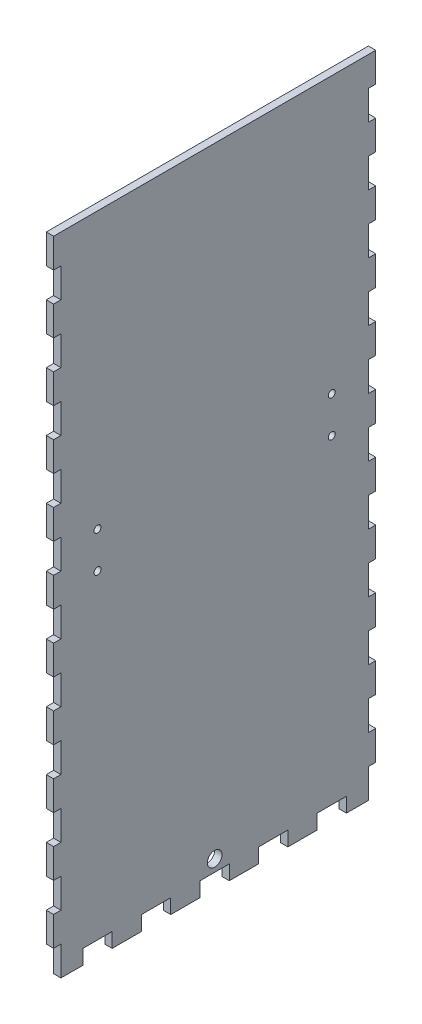
SolidWorks part; units mm, degrees
material "Acrylic (Medium-high impact)"
ref_plane "Front Plane" through (0, 0, 0) normal (0, 0, 1) x (1, 0, 0)
ref_plane "Top Plane" through (0, 0, 0) normal (0, 1, 0) x (1, 0, 0)
ref_plane "Right Plane" through (0, 0, 0) normal (1, 0, 0) x (0, 0, -1)
sketch "Sketch1" plane through (0, 0, 0) normal (0, 1, 0) x (1, 0, 0)
  line L1 (-241.7445, 69.85) -> (241.7445, 69.85)
  line L2 (-241.7445, 69.85) -> (-241.7445, -69.85)
  line L3 (-241.7445, -69.85) -> (241.7445, -69.85)
  line L4 (241.7445, 69.85) -> (241.7445, -69.85)
  point P4 (-241.7445, 0)
  point P6 (0, 69.85)
  dimension "D1" = 139.7
  dimension "D2" = 483.489
extrude "Boss-Extrude1" add sketch "Sketch1" along normal blind 6.35
sketch "Sketch2" plane through (0, 6.35, 0) normal (0, 1, 0) x (1, 0, 0)
  line L0 (241.7445, -69.85) -> (241.7445, 69.85) construction
  line L1 (-241.7445, 69.85) -> (241.7445, 69.85)
  line L2 (-241.7445, 69.85) -> (-241.7445, -69.85)
  line L3 (-241.7445, -69.85) -> (241.7445, -69.85)
  line L4 (241.7445, 69.85) -> (241.7445, -69.85)
  line L5 (-241.7445, -69.85) -> (241.7445, -69.85) construction
  line L7 (-238.5695, 66.675) -> (238.5695, 66.675)
  line L8 (-238.5695, 66.675) -> (-238.5695, -66.675)
  line L9 (-238.5695, -66.675) -> (238.5695, -66.675)
  line L10 (238.5695, 66.675) -> (238.5695, -66.675)
  point P7 (-238.5695, 0)
  point P14 (-241.7445, 0)
  point P15 (0, -66.675)
  point P16 (0, -69.85)
  point P17 (238.5695, 0)
  point P18 (241.7445, 0)
  dimension "D1" = 3.175
  dimension "D2" = 3.175
extrude "Boss-Extrude2" add sketch "Sketch2" along normal blind 299.212
sketch "Sketch3" plane through (0, 0, 69.85) normal (0, 0, 1) x (1, 0, 0)
  line L0 (79.8195, 305.562) -> (79.8195, 0) construction
  line L2 (-238.5695, 6.35) -> (238.5695, 6.35) construction
  line L4 (76.5175, 292.354) -> (76.5175, 6.35)
  line L5 (76.5175, 6.35) -> (83.1215, 6.35)
  line L6 (83.1215, 283.2407) -> (83.1215, 6.35)
  line L11 (83.1215, 101.6) -> (69.4055, 101.6) construction
  line L12 (-241.7445, 0) -> (241.7445, 0) construction
  line L13 (66.6115, 88.9) -> (66.6115, 101.6) construction
  line L14 (63.8175, 88.9) -> (69.4055, 88.9)
  line L15 (63.8175, 88.9) -> (63.8175, 71.9667)
  line L16 (63.8175, 71.9667) -> (69.4055, 71.9667)
  line L17 (69.4055, 88.9) -> (69.4055, 71.9667)
  line L18 (63.8175, 42.3333) -> (69.4055, 42.3333)
  line L19 (63.8175, 42.3333) -> (63.8175, 59.2667)
  line L20 (63.8175, 59.2667) -> (69.4055, 59.2667)
  line L21 (69.4055, 42.3333) -> (69.4055, 59.2667)
  line L26 (63.8175, 29.6333) -> (69.4055, 29.6333)
  line L27 (63.8175, 29.6333) -> (63.8175, 12.7)
  line L28 (63.8175, 12.7) -> (69.4055, 12.7)
  line L29 (69.4055, 29.6333) -> (69.4055, 12.7)
  line L30 (66.6115, 59.2667) -> (66.6115, 71.9667) construction
  line L31 (66.6115, 29.6333) -> (66.6115, 42.3333) construction
  line L32 (66.6115, 12.7) -> (66.6115, 0) construction
  line L33 (-241.7445, 305.562) -> (241.7445, 305.562) construction
  line L34 (-83.1215, 283.2407) -> (-83.1215, 6.35)
  line L35 (-83.1215, 6.35) -> (-76.5175, 6.35)
  line L36 (-76.5175, 292.354) -> (-76.5175, 6.35)
  line L37 (-76.5175, 292.354) -> (-96.0755, 292.354)
  line L38 (-85.6615, 285.7807) -> (-96.0755, 285.7807)
  line L39 (-96.0755, 292.354) -> (-96.0755, 285.7807)
  line L40 (-76.5175, 101.6) -> (-63.8175, 101.6) construction
  line L41 (-66.6115, 88.9) -> (-66.6115, 101.6) construction
  line L42 (-69.4055, 88.9) -> (-63.8175, 88.9)
  line L43 (-69.4055, 88.9) -> (-69.4055, 71.9667)
  line L44 (-69.4055, 71.9667) -> (-63.8175, 71.9667)
  line L45 (-63.8175, 88.9) -> (-63.8175, 71.9667)
  line L46 (-69.4055, 42.3333) -> (-63.8175, 42.3333)
  line L47 (-69.4055, 42.3333) -> (-69.4055, 59.2667)
  line L48 (-69.4055, 59.2667) -> (-63.8175, 59.2667)
  line L49 (-63.8175, 42.3333) -> (-63.8175, 59.2667)
  line L50 (-69.4055, 29.6333) -> (-63.8175, 29.6333)
  line L51 (-69.4055, 29.6333) -> (-69.4055, 12.7)
  line L52 (-69.4055, 12.7) -> (-63.8175, 12.7)
  line L53 (-63.8175, 29.6333) -> (-63.8175, 12.7)
  line L54 (-66.6115, 59.2667) -> (-66.6115, 71.9667) construction
  line L55 (-66.6115, 29.6333) -> (-66.6115, 42.3333) construction
  line L56 (-66.6115, 12.7) -> (-66.6115, 0) construction
  line L58 (76.5175, 292.354) -> (96.0755, 292.354)
  line L59 (96.0755, 292.354) -> (96.0755, 285.7807)
  line L60 (85.6615, 285.7807) -> (96.0755, 285.7807)
  line L61 (-241.7445, 305.562) -> (-241.7445, 0) construction
  line L62 (241.7445, 305.562) -> (241.7445, 0) construction
  arc A1 (-83.1215, 283.2407) -> (-85.6615, 285.7807) centre (-85.6615, 283.2407) ccw
  arc A2 (85.6615, 285.7807) -> (83.1215, 283.2407) centre (85.6615, 283.2407) ccw
  point P5 (79.8195, 6.35)
  dimension "D14" = 2.54
  dimension "D1" = 6.604
  dimension "D2" = 6.5733
  dimension "D3" = 158.623
  dimension "D4" = 158.623
  dimension "D6" = 101.6
  dimension "D7" = 12.7
  dimension "D8" = 12.7
  dimension "D9" = 5.588
  dimension "D11" = 6.604
  dimension "D12" = 12.954
  dimension "D13" = 286.004
  dimension "D15" = 12.7
  dimension "D16" = 12.7
  dimension "D17" = 5.588
extrude "Door Slot" cut sketch "Sketch3" against normal blind 12.7
sketch "Sketch4" plane through (0, 0, -66.675) normal (0, 0, 1) x (1, 0, 0)
  line L0 (-241.7445, 305.562) -> (241.7445, 305.562) construction
  line L1 (70.1675, 305.562) -> (76.5175, 305.562)
  line L2 (70.1675, 305.562) -> (70.1675, 6.35)
  line L3 (70.1675, 6.35) -> (76.5175, 6.35)
  line L4 (76.5175, 305.562) -> (76.5175, 6.35)
  line L5 (99.2505, 264.2108) -> (99.2505, 248.2596) construction
  line L7 (96.0755, 305.562) -> (102.4255, 305.562)
  line L8 (96.0755, 305.562) -> (96.0755, 6.35)
  line L9 (96.0755, 6.35) -> (102.4255, 6.35)
  line L10 (102.4255, 305.562) -> (102.4255, 6.35)
  line L11 (238.5695, 6.35) -> (-238.5695, 6.35) construction
  line L13 (76.5175, 305.562) -> (70.1675, 305.562)
  line L14 (76.5175, 305.562) -> (76.5175, 292.862)
  line L15 (76.5175, 292.862) -> (70.1675, 292.862)
  line L16 (70.1675, 305.562) -> (70.1675, 292.862)
  line L17 (76.5175, 276.9108) -> (70.1675, 276.9108)
  line L18 (76.5175, 276.9108) -> (76.5175, 264.2108)
  line L19 (76.5175, 264.2108) -> (70.1675, 264.2108)
  line L20 (70.1675, 276.9108) -> (70.1675, 264.2108)
  line L21 (70.1675, 6.35) -> (76.5175, 6.35)
  line L22 (70.1675, 6.35) -> (70.1675, 19.05)
  line L23 (70.1675, 19.05) -> (76.5175, 19.05)
  line L24 (76.5175, 6.35) -> (76.5175, 19.05)
  line L25 (70.1675, 35.0012) -> (76.5175, 35.0012)
  line L26 (70.1675, 35.0012) -> (70.1675, 47.7012)
  line L27 (70.1675, 47.7012) -> (76.5175, 47.7012)
  line L28 (76.5175, 35.0012) -> (76.5175, 47.7012)
  line L29 (70.1675, 92.3036) -> (76.5175, 92.3036)
  line L30 (70.1675, 92.3036) -> (70.1675, 105.0036)
  line L31 (70.1675, 105.0036) -> (76.5175, 105.0036)
  line L32 (76.5175, 92.3036) -> (76.5175, 105.0036)
  line L33 (70.1675, 149.606) -> (76.5175, 149.606)
  line L34 (70.1675, 149.606) -> (70.1675, 162.306)
  line L35 (70.1675, 162.306) -> (76.5175, 162.306)
  line L36 (76.5175, 149.606) -> (76.5175, 162.306)
  line L37 (70.1675, 178.2572) -> (76.5175, 178.2572)
  line L38 (70.1675, 178.2572) -> (70.1675, 190.9572)
  line L39 (70.1675, 190.9572) -> (76.5175, 190.9572)
  line L40 (76.5175, 178.2572) -> (76.5175, 190.9572)
  line L41 (70.1675, 206.9084) -> (76.5175, 206.9084)
  line L42 (70.1675, 206.9084) -> (70.1675, 219.6084)
  line L43 (70.1675, 219.6084) -> (76.5175, 219.6084)
  line L44 (76.5175, 206.9084) -> (76.5175, 219.6084)
  line L45 (70.1675, 235.5596) -> (76.5175, 235.5596)
  line L46 (70.1675, 235.5596) -> (70.1675, 248.2596)
  line L47 (70.1675, 248.2596) -> (76.5175, 248.2596)
  line L48 (76.5175, 235.5596) -> (76.5175, 248.2596)
  line L49 (76.5175, 133.6548) -> (70.1675, 133.6548)
  line L50 (76.5175, 133.6548) -> (76.5175, 120.9548)
  line L51 (76.5175, 120.9548) -> (70.1675, 120.9548)
  line L52 (70.1675, 133.6548) -> (70.1675, 120.9548)
  line L53 (76.5175, 76.3524) -> (70.1675, 76.3524)
  line L54 (76.5175, 76.3524) -> (76.5175, 63.6524)
  line L55 (76.5175, 63.6524) -> (70.1675, 63.6524)
  line L56 (70.1675, 76.3524) -> (70.1675, 63.6524)
  line L57 (73.3425, 305.562) -> (73.3425, 292.862) construction
  line L58 (73.3425, 292.862) -> (73.3425, 276.9108) construction
  line L59 (73.3425, 276.9108) -> (73.3425, 264.2108) construction
  line L60 (73.3425, 248.2596) -> (73.3425, 235.5596) construction
  line L61 (73.3425, 235.5596) -> (73.3425, 219.6084) construction
  line L62 (73.3425, 219.6084) -> (73.3425, 206.9084) construction
  line L63 (73.3425, 206.9084) -> (73.3425, 190.9572) construction
  line L64 (73.3425, 190.9572) -> (73.3425, 178.2572) construction
  line L65 (73.3425, 178.2572) -> (73.3425, 162.306) construction
  line L66 (73.3425, 162.306) -> (73.3425, 149.606) construction
  line L67 (73.3425, 133.6548) -> (73.3425, 120.9548) construction
  line L68 (73.3425, 120.9548) -> (73.3425, 105.0036) construction
  line L69 (73.3425, 105.0036) -> (73.3425, 92.3036) construction
  line L70 (73.3425, 92.3036) -> (73.3425, 76.3524) construction
  line L71 (73.3425, 76.3524) -> (73.3425, 63.6524) construction
  line L72 (73.3425, 63.6524) -> (73.3425, 47.7012) construction
  line L73 (73.3425, 47.7012) -> (73.3425, 35.0012) construction
  line L74 (73.3425, 35.0012) -> (73.3425, 19.05) construction
  line L75 (73.3425, 19.05) -> (73.3425, 6.35) construction
  line L76 (73.3425, 149.606) -> (73.3425, 133.6548) construction
  line L77 (73.3425, 264.2108) -> (73.3425, 248.2596) construction
  line L78 (86.2965, 305.562) -> (86.2965, 0) construction
  line L79 (241.7445, 305.562) -> (-241.7445, 305.562) construction
  line L80 (241.7445, 0) -> (-241.7445, 0) construction
  line L81 (86.2965, 15.1854) -> (96.0755, 15.1854) construction
  line L82 (86.2965, 15.1854) -> (76.5175, 15.1854) construction
  line L83 (99.2505, 149.606) -> (99.2505, 133.6548) construction
  line L84 (99.2505, 19.05) -> (99.2505, 6.35) construction
  line L85 (99.2505, 35.0012) -> (99.2505, 19.05) construction
  line L86 (99.2505, 47.7012) -> (99.2505, 35.0012) construction
  line L87 (99.2505, 63.6524) -> (99.2505, 47.7012) construction
  line L88 (99.2505, 76.3524) -> (99.2505, 63.6524) construction
  line L89 (99.2505, 92.3036) -> (99.2505, 76.3524) construction
  line L90 (99.2505, 105.0036) -> (99.2505, 92.3036) construction
  line L91 (99.2505, 120.9548) -> (99.2505, 105.0036) construction
  line L92 (99.2505, 133.6548) -> (99.2505, 120.9548) construction
  line L93 (99.2505, 162.306) -> (99.2505, 149.606) construction
  line L94 (99.2505, 178.2572) -> (99.2505, 162.306) construction
  line L95 (99.2505, 190.9572) -> (99.2505, 178.2572) construction
  line L96 (99.2505, 206.9084) -> (99.2505, 190.9572) construction
  line L97 (99.2505, 219.6084) -> (99.2505, 206.9084) construction
  line L98 (99.2505, 235.5596) -> (99.2505, 219.6084) construction
  line L99 (99.2505, 248.2596) -> (99.2505, 235.5596) construction
  line L100 (99.2505, 276.9108) -> (99.2505, 264.2108) construction
  line L101 (99.2505, 292.862) -> (99.2505, 276.9108) construction
  line L102 (99.2505, 305.562) -> (99.2505, 292.862) construction
  line L103 (102.4255, 76.3524) -> (102.4255, 63.6524)
  line L104 (96.0755, 63.6524) -> (102.4255, 63.6524)
  line L105 (96.0755, 76.3524) -> (96.0755, 63.6524)
  line L106 (96.0755, 76.3524) -> (102.4255, 76.3524)
  line L107 (102.4255, 133.6548) -> (102.4255, 120.9548)
  line L108 (96.0755, 120.9548) -> (102.4255, 120.9548)
  line L109 (96.0755, 133.6548) -> (96.0755, 120.9548)
  line L110 (96.0755, 133.6548) -> (102.4255, 133.6548)
  line L111 (96.0755, 235.5596) -> (96.0755, 248.2596)
  line L112 (102.4255, 248.2596) -> (96.0755, 248.2596)
  line L113 (102.4255, 235.5596) -> (102.4255, 248.2596)
  line L114 (102.4255, 235.5596) -> (96.0755, 235.5596)
  line L115 (96.0755, 206.9084) -> (96.0755, 219.6084)
  line L116 (102.4255, 219.6084) -> (96.0755, 219.6084)
  line L117 (102.4255, 206.9084) -> (102.4255, 219.6084)
  line L118 (102.4255, 206.9084) -> (96.0755, 206.9084)
  line L119 (96.0755, 178.2572) -> (96.0755, 190.9572)
  line L120 (102.4255, 190.9572) -> (96.0755, 190.9572)
  line L121 (102.4255, 178.2572) -> (102.4255, 190.9572)
  line L122 (102.4255, 178.2572) -> (96.0755, 178.2572)
  line L123 (96.0755, 149.606) -> (96.0755, 162.306)
  line L124 (102.4255, 162.306) -> (96.0755, 162.306)
  line L125 (102.4255, 149.606) -> (102.4255, 162.306)
  line L126 (102.4255, 149.606) -> (96.0755, 149.606)
  line L127 (96.0755, 92.3036) -> (96.0755, 105.0036)
  line L128 (102.4255, 105.0036) -> (96.0755, 105.0036)
  line L129 (102.4255, 92.3036) -> (102.4255, 105.0036)
  line L130 (102.4255, 92.3036) -> (96.0755, 92.3036)
  line L131 (96.0755, 35.0012) -> (96.0755, 47.7012)
  line L132 (102.4255, 47.7012) -> (96.0755, 47.7012)
  line L133 (102.4255, 35.0012) -> (102.4255, 47.7012)
  line L134 (102.4255, 35.0012) -> (96.0755, 35.0012)
  line L135 (96.0755, 6.35) -> (96.0755, 19.05)
  line L136 (102.4255, 19.05) -> (96.0755, 19.05)
  line L137 (102.4255, 6.35) -> (102.4255, 19.05)
  line L138 (102.4255, 6.35) -> (96.0755, 6.35)
  line L139 (102.4255, 276.9108) -> (102.4255, 264.2108)
  line L140 (96.0755, 264.2108) -> (102.4255, 264.2108)
  line L141 (96.0755, 276.9108) -> (96.0755, 264.2108)
  line L142 (96.0755, 276.9108) -> (102.4255, 276.9108)
  line L143 (102.4255, 305.562) -> (102.4255, 292.862)
  line L144 (96.0755, 292.862) -> (102.4255, 292.862)
  line L145 (96.0755, 305.562) -> (96.0755, 292.862)
  line L146 (96.0755, 305.562) -> (102.4255, 305.562)
  line L147 (96.0755, 305.562) -> (96.0755, 6.35)
  line L148 (102.4255, 6.35) -> (96.0755, 6.35)
  line L149 (102.4255, 305.562) -> (102.4255, 6.35)
  line L150 (102.4255, 305.562) -> (96.0755, 305.562)
  line L151 (-102.4255, 305.562) -> (-96.0755, 305.562)
  line L152 (-102.4255, 305.562) -> (-102.4255, 6.35)
  line L153 (-102.4255, 6.35) -> (-96.0755, 6.35)
  line L154 (-96.0755, 305.562) -> (-96.0755, 6.35)
  line L155 (-73.3425, 264.2108) -> (-73.3425, 248.2596) construction
  line L156 (-76.5175, 305.562) -> (-70.1675, 305.562)
  line L157 (-76.5175, 305.562) -> (-76.5175, 6.35)
  line L158 (-76.5175, 6.35) -> (-70.1675, 6.35)
  line L159 (-70.1675, 305.562) -> (-70.1675, 6.35)
  line L160 (-96.0755, 305.562) -> (-102.4255, 305.562)
  line L161 (-96.0755, 305.562) -> (-96.0755, 292.862)
  line L162 (-96.0755, 292.862) -> (-102.4255, 292.862)
  line L163 (-102.4255, 305.562) -> (-102.4255, 292.862)
  line L164 (-96.0755, 276.9108) -> (-102.4255, 276.9108)
  line L165 (-96.0755, 276.9108) -> (-96.0755, 264.2108)
  line L166 (-96.0755, 264.2108) -> (-102.4255, 264.2108)
  line L167 (-102.4255, 276.9108) -> (-102.4255, 264.2108)
  line L168 (-102.4255, 6.35) -> (-96.0755, 6.35)
  line L169 (-102.4255, 6.35) -> (-102.4255, 19.05)
  line L170 (-102.4255, 19.05) -> (-96.0755, 19.05)
  line L171 (-96.0755, 6.35) -> (-96.0755, 19.05)
  line L172 (-102.4255, 35.0012) -> (-96.0755, 35.0012)
  line L173 (-102.4255, 35.0012) -> (-102.4255, 47.7012)
  line L174 (-102.4255, 47.7012) -> (-96.0755, 47.7012)
  line L175 (-96.0755, 35.0012) -> (-96.0755, 47.7012)
  line L176 (-102.4255, 92.3036) -> (-96.0755, 92.3036)
  line L177 (-102.4255, 92.3036) -> (-102.4255, 105.0036)
  line L178 (-102.4255, 105.0036) -> (-96.0755, 105.0036)
  line L179 (-96.0755, 92.3036) -> (-96.0755, 105.0036)
  line L180 (-102.4255, 149.606) -> (-96.0755, 149.606)
  line L181 (-102.4255, 149.606) -> (-102.4255, 162.306)
  line L182 (-102.4255, 162.306) -> (-96.0755, 162.306)
  line L183 (-96.0755, 149.606) -> (-96.0755, 162.306)
  line L184 (-102.4255, 178.2572) -> (-96.0755, 178.2572)
  line L185 (-102.4255, 178.2572) -> (-102.4255, 190.9572)
  line L186 (-102.4255, 190.9572) -> (-96.0755, 190.9572)
  line L187 (-96.0755, 178.2572) -> (-96.0755, 190.9572)
  line L188 (-102.4255, 206.9084) -> (-96.0755, 206.9084)
  line L189 (-102.4255, 206.9084) -> (-102.4255, 219.6084)
  line L190 (-102.4255, 219.6084) -> (-96.0755, 219.6084)
  line L191 (-96.0755, 206.9084) -> (-96.0755, 219.6084)
  line L192 (-102.4255, 235.5596) -> (-96.0755, 235.5596)
  line L193 (-102.4255, 235.5596) -> (-102.4255, 248.2596)
  line L194 (-102.4255, 248.2596) -> (-96.0755, 248.2596)
  line L195 (-96.0755, 235.5596) -> (-96.0755, 248.2596)
  line L196 (-96.0755, 133.6548) -> (-102.4255, 133.6548)
  line L197 (-96.0755, 133.6548) -> (-96.0755, 120.9548)
  line L198 (-96.0755, 120.9548) -> (-102.4255, 120.9548)
  line L199 (-102.4255, 133.6548) -> (-102.4255, 120.9548)
  line L200 (-96.0755, 76.3524) -> (-102.4255, 76.3524)
  line L201 (-96.0755, 76.3524) -> (-96.0755, 63.6524)
  line L202 (-96.0755, 63.6524) -> (-102.4255, 63.6524)
  line L203 (-102.4255, 76.3524) -> (-102.4255, 63.6524)
  line L204 (-99.2505, 305.562) -> (-99.2505, 292.862) construction
  line L205 (-99.2505, 292.862) -> (-99.2505, 276.9108) construction
  line L206 (-99.2505, 276.9108) -> (-99.2505, 264.2108) construction
  line L207 (-99.2505, 248.2596) -> (-99.2505, 235.5596) construction
  line L208 (-99.2505, 235.5596) -> (-99.2505, 219.6084) construction
  line L209 (-99.2505, 219.6084) -> (-99.2505, 206.9084) construction
  line L210 (-99.2505, 206.9084) -> (-99.2505, 190.9572) construction
  line L211 (-99.2505, 190.9572) -> (-99.2505, 178.2572) construction
  line L212 (-99.2505, 178.2572) -> (-99.2505, 162.306) construction
  line L213 (-99.2505, 162.306) -> (-99.2505, 149.606) construction
  line L214 (-99.2505, 133.6548) -> (-99.2505, 120.9548) construction
  line L215 (-99.2505, 120.9548) -> (-99.2505, 105.0036) construction
  line L216 (-99.2505, 105.0036) -> (-99.2505, 92.3036) construction
  line L217 (-99.2505, 92.3036) -> (-99.2505, 76.3524) construction
  line L218 (-99.2505, 76.3524) -> (-99.2505, 63.6524) construction
  line L219 (-99.2505, 63.6524) -> (-99.2505, 47.7012) construction
  line L220 (-99.2505, 47.7012) -> (-99.2505, 35.0012) construction
  line L221 (-99.2505, 35.0012) -> (-99.2505, 19.05) construction
  line L222 (-99.2505, 19.05) -> (-99.2505, 6.35) construction
  line L223 (-99.2505, 149.606) -> (-99.2505, 133.6548) construction
  line L224 (-99.2505, 264.2108) -> (-99.2505, 248.2596) construction
  line L225 (-86.2965, 305.562) -> (-86.2965, 0) construction
  line L226 (-86.2965, 341.727) -> (-76.5175, 341.727) construction
  line L227 (-86.2965, 341.727) -> (-96.0755, 341.727) construction
  line L228 (-73.3425, 149.606) -> (-73.3425, 133.6548) construction
  line L229 (-73.3425, 19.05) -> (-73.3425, 6.35) construction
  line L230 (-73.3425, 35.0012) -> (-73.3425, 19.05) construction
  line L231 (-73.3425, 47.7012) -> (-73.3425, 35.0012) construction
  line L232 (-73.3425, 63.6524) -> (-73.3425, 47.7012) construction
  line L233 (-73.3425, 76.3524) -> (-73.3425, 63.6524) construction
  line L234 (-73.3425, 92.3036) -> (-73.3425, 76.3524) construction
  line L235 (-73.3425, 105.0036) -> (-73.3425, 92.3036) construction
  line L236 (-73.3425, 120.9548) -> (-73.3425, 105.0036) construction
  line L237 (-73.3425, 133.6548) -> (-73.3425, 120.9548) construction
  line L238 (-73.3425, 162.306) -> (-73.3425, 149.606) construction
  line L239 (-73.3425, 178.2572) -> (-73.3425, 162.306) construction
  line L240 (-73.3425, 190.9572) -> (-73.3425, 178.2572) construction
  line L241 (-73.3425, 206.9084) -> (-73.3425, 190.9572) construction
  line L242 (-73.3425, 219.6084) -> (-73.3425, 206.9084) construction
  line L243 (-73.3425, 235.5596) -> (-73.3425, 219.6084) construction
  line L244 (-73.3425, 248.2596) -> (-73.3425, 235.5596) construction
  line L245 (-73.3425, 276.9108) -> (-73.3425, 264.2108) construction
  line L246 (-73.3425, 292.862) -> (-73.3425, 276.9108) construction
  line L247 (-73.3425, 305.562) -> (-73.3425, 292.862) construction
  line L248 (-70.1675, 76.3524) -> (-70.1675, 63.6524)
  line L249 (-76.5175, 63.6524) -> (-70.1675, 63.6524)
  line L250 (-76.5175, 76.3524) -> (-76.5175, 63.6524)
  line L251 (-76.5175, 76.3524) -> (-70.1675, 76.3524)
  line L252 (-70.1675, 133.6548) -> (-70.1675, 120.9548)
  line L253 (-76.5175, 120.9548) -> (-70.1675, 120.9548)
  line L254 (-76.5175, 133.6548) -> (-76.5175, 120.9548)
  line L255 (-76.5175, 133.6548) -> (-70.1675, 133.6548)
  line L256 (-76.5175, 235.5596) -> (-76.5175, 248.2596)
  line L257 (-70.1675, 248.2596) -> (-76.5175, 248.2596)
  line L258 (-70.1675, 235.5596) -> (-70.1675, 248.2596)
  line L259 (-70.1675, 235.5596) -> (-76.5175, 235.5596)
  line L260 (-76.5175, 206.9084) -> (-76.5175, 219.6084)
  line L261 (-70.1675, 219.6084) -> (-76.5175, 219.6084)
  line L262 (-70.1675, 206.9084) -> (-70.1675, 219.6084)
  line L263 (-70.1675, 206.9084) -> (-76.5175, 206.9084)
  line L264 (-76.5175, 178.2572) -> (-76.5175, 190.9572)
  line L265 (-70.1675, 190.9572) -> (-76.5175, 190.9572)
  line L266 (-70.1675, 178.2572) -> (-70.1675, 190.9572)
  line L267 (-70.1675, 178.2572) -> (-76.5175, 178.2572)
  line L268 (-76.5175, 149.606) -> (-76.5175, 162.306)
  line L269 (-70.1675, 162.306) -> (-76.5175, 162.306)
  line L270 (-70.1675, 149.606) -> (-70.1675, 162.306)
  line L271 (-70.1675, 149.606) -> (-76.5175, 149.606)
  line L272 (-76.5175, 92.3036) -> (-76.5175, 105.0036)
  line L273 (-70.1675, 105.0036) -> (-76.5175, 105.0036)
  line L274 (-70.1675, 92.3036) -> (-70.1675, 105.0036)
  line L275 (-70.1675, 92.3036) -> (-76.5175, 92.3036)
  line L276 (-76.5175, 35.0012) -> (-76.5175, 47.7012)
  line L277 (-70.1675, 47.7012) -> (-76.5175, 47.7012)
  line L278 (-70.1675, 35.0012) -> (-70.1675, 47.7012)
  line L279 (-70.1675, 35.0012) -> (-76.5175, 35.0012)
  line L280 (-76.5175, 6.35) -> (-76.5175, 19.05)
  line L281 (-70.1675, 19.05) -> (-76.5175, 19.05)
  line L282 (-70.1675, 6.35) -> (-70.1675, 19.05)
  line L283 (-70.1675, 6.35) -> (-76.5175, 6.35)
  line L284 (-70.1675, 276.9108) -> (-70.1675, 264.2108)
  line L285 (-76.5175, 264.2108) -> (-70.1675, 264.2108)
  line L286 (-76.5175, 276.9108) -> (-76.5175, 264.2108)
  line L287 (-76.5175, 276.9108) -> (-70.1675, 276.9108)
  line L288 (-70.1675, 305.562) -> (-70.1675, 292.862)
  line L289 (-76.5175, 292.862) -> (-70.1675, 292.862)
  line L290 (-76.5175, 305.562) -> (-76.5175, 292.862)
  line L291 (-76.5175, 305.562) -> (-70.1675, 305.562)
  line L292 (-76.5175, 305.562) -> (-76.5175, 6.35)
  line L293 (-70.1675, 6.35) -> (-76.5175, 6.35)
  line L294 (-70.1675, 305.562) -> (-70.1675, 6.35)
  line L295 (-70.1675, 305.562) -> (-76.5175, 305.562)
  line L296 (-241.7445, 0) -> (241.7445, 0) construction
  line L297 (-96.0755, 292.354) -> (-96.0755, 285.7807) construction
  line L298 (-76.5175, 6.35) -> (-76.5175, 292.354) construction
  line L299 (76.5175, 292.354) -> (76.5175, 6.35) construction
  line L300 (96.0755, 285.7807) -> (96.0755, 292.354) construction
  dimension "D1" = 6.35
  dimension "D2" = 12.7
  dimension "D3" = 6.35
  dimension "D4" = 12.7
extrude "Door Guide Holes" cut sketch "Sketch4" against normal up to next (3.175 mm away) contours L2 L47 L4 L19 | L45 L2 L43 L4 | L41 L2 L39 L4 | L37 L2 L35 L4 | L49 L4 L33 L2 | L4 L51 L2 L31 | L53 L4 L29 L2 | L4 L55 L2 L27 | L25 L2 L23 L4 | L164 L154 L162 L152 | L152 L194 L154 L166 | L192 L152 L190 L154 | L188 L152 L186 L154 | L184 L152 L182 L154 | L196 L154 L180 L152 | L154 L198 L152 L178 | L200 L154 L176 L152 | L154 L202 L152 L174 | L172 L152 L170 L154 | L144 L8 L142 L10 | L140 L8 L112 L10 | L116 L10 L114 L8 | L120 L10 L118 L8 | L124 L10 L122 L8 | L10 L126 L8 L110 | L128 L10 L108 L8 | L10 L130 L8 L106 | L132 L10 L104 L8 | L136 L10 L134 L8 | L289 L157 L287 L159 | L285 L157 L257 L159 | L261 L159 L259 L157 | L265 L159 L263 L157 | L269 L159 L267 L157 | L159 L271 L157 L255 | L273 L159 L253 L157 | L159 L275 L157 L251 | L277 L159 L249 L157 | L281 L159 L279 L157 | L17 L4 L15 L2 region at (73.3425, 284.8864, -66.675) region at (73.3425, 256.2352, -66.675) region at (73.3425, 227.584, -66.675) region at (73.3425, 198.9328, -66.675) region at (73.3425, 170.2816, -66.675) region at (73.3425, 141.6304, -66.675) region at (73.3425, 112.9792, -66.675) region at (73.3425, 84.328, -66.675) region at (73.3425, 55.6768, -66.675) region at (73.3425, 27.0256, -66.675) region at (99.2505, 284.8864, -66.675) region at (99.2505, 256.2352, -66.675) region at (99.2505, 227.584, -66.675) region at (99.2505, 198.9328, -66.675) region at (99.2505, 170.2816, -66.675) region at (99.2505, 141.6304, -66.675) region at (99.2505, 112.9792, -66.675) region at (99.2505, 84.328, -66.675) region at (99.2505, 55.6768, -66.675) region at (99.2505, 27.0256, -66.675) region at (-99.2505, 284.8864, -66.675) region at (-99.2505, 256.2352, -66.675) region at (-99.2505, 227.584, -66.675) region at (-99.2505, 198.9328, -66.675) region at (-99.2505, 170.2816, -66.675) region at (-99.2505, 141.6304, -66.675) region at (-99.2505, 112.9792, -66.675) region at (-99.2505, 84.328, -66.675) region at (-99.2505, 55.6768, -66.675) region at (-99.2505, 27.0256, -66.675) region at (-73.3425, 284.8864, -66.675) region at (-73.3425, 256.2352, -66.675) region at (-73.3425, 227.584, -66.675) region at (-73.3425, 198.9328, -66.675) region at (-73.3425, 170.2816, -66.675) region at (-73.3425, 141.6304, -66.675) region at (-73.3425, 112.9792, -66.675) region at (-73.3425, 84.328, -66.675) region at (-73.3425, 55.6768, -66.675) region at (-73.3425, 27.0256, -66.675)
sketch "Lever Holes" plane through (0, 0, -69.85) normal (0, 0, 1) x (1, 0, 0)
  line L0 (-59.6175, 37.685) -> (-34.2175, 37.685)
  line L1 (-59.6175, 37.685) -> (-59.6175, 30.065)
  line L2 (-59.6175, 30.065) -> (-34.2175, 30.065)
  line L3 (-34.2175, 37.685) -> (-34.2175, 30.065)
  line L4 (-60.1675, 16.35) -> (-56.1675, 16.35)
  line L5 (-60.1675, 16.35) -> (-60.1675, 10)
  line L6 (-60.1675, 10) -> (-56.1675, 10)
  line L7 (-56.1675, 16.35) -> (-56.1675, 10)
  line L8 (-14.1675, 16.35) -> (-10.1675, 16.35)
  line L9 (-14.1675, 16.35) -> (-14.1675, 10)
  line L10 (-14.1675, 10) -> (-10.1675, 10)
  line L11 (-10.1675, 16.35) -> (-10.1675, 10)
  line L12 (-56.1675, 13.175) -> (-14.1675, 13.175) construction
  line L13 (83.1215, 6.35) -> (83.1215, 283.2407) construction
  line L14 (83.1215, 6.35) -> (238.5695, 6.35) construction
  line L15 (238.5695, 6.35) -> (-238.5695, 6.35) construction
  line L16 (222.6945, 160.655) -> (222.6945, 144.907) construction
  line L17 (241.7445, 305.562) -> (241.7445, 0) construction
  line L18 (0, -76.835) -> (0, 76.835) construction
  line L19 (83.1215, 152.3404) -> (-83.1215, 152.3404) construction
  line L20 (-83.1215, 283.2407) -> (-83.1215, 6.35) construction
  line L21 (0, 171.6172) -> (0, 111.8135) construction
  line L22 (14.1675, 16.35) -> (14.1675, 10)
  line L23 (14.1675, 10) -> (10.1675, 10)
  line L24 (10.1675, 16.35) -> (10.1675, 10)
  line L25 (14.1675, 16.35) -> (10.1675, 16.35)
  line L26 (59.6175, 37.685) -> (59.6175, 30.065)
  line L27 (59.6175, 30.065) -> (34.2175, 30.065)
  line L28 (34.2175, 37.685) -> (34.2175, 30.065)
  line L29 (59.6175, 37.685) -> (34.2175, 37.685)
  line L30 (60.1675, 16.35) -> (60.1675, 10)
  line L31 (60.1675, 10) -> (56.1675, 10)
  line L32 (56.1675, 16.35) -> (56.1675, 10)
  line L33 (60.1675, 16.35) -> (56.1675, 16.35)
  line L35 (70.1675, 19.05) -> (70.1675, 35.0012) construction
  circle A0 centre (222.6945, 160.655) radius 1.5
  circle A1 centre (222.6945, 144.907) radius 1.5
  circle A2 centre (-222.6945, 160.655) radius 1.5
  circle A3 centre (-222.6945, 144.907) radius 1.5
  point P13 (-46.9175, 30.065)
  point P31 (222.6945, 152.781)
  point P32 (241.7445, 152.781)
  dimension "D10" = 3
  dimension "D1" = 25.4
  dimension "D2" = 7.62
  dimension "D3" = 4
  dimension "D4" = 6.35
  dimension "D5" = 42
  dimension "D6" = 31.335
  dimension "D7" = 10
  dimension "D8" = 10
  dimension "D9" = 13.25
  dimension "D11" = 15.748
  dimension "D12" = 19.05
extrude "LeverHole Cut" cut sketch "Lever Holes" along normal up to next
extrude "Lbracket Thru Holes" cut sketch "Lever Holes<2>" along normal through all contours A2 | A3 | A0 | A1 | A2 | A3 | A0 | A1 region at (222.6945, 160.655, -69.85) region at (222.6945, 144.907, -69.85) region at (-222.6945, 160.655, -69.85) region at (-222.6945, 144.907, -69.85)
sketch "Lever Holes<2>" plane through (0, 0, -69.85) normal (0, 0, 1) x (1, 0, 0) same geometry as "Lever Holes"
sketch "Sketch8" plane through (-241.7445, 0, 0) normal (-1, 0, 0) x (0, 0, 1)
  line L0 (-69.85, 0) -> (69.85, 0) construction
  circle A0 centre (0, 11.43) radius 3.175
  point P6 (0, 0)
  dimension "D1" = 6.35
  dimension "D2" = 11.43
extrude "Tether Hole" cut sketch "Sketch8" against normal through all
sketch "Sketch16" plane through (0, 0, 69.85) normal (0, 0, 1) x (1, 0, 0)
  line L1 (58.8645, 275.3979) -> (113.7285, 275.3979)
  line L2 (58.8645, 275.3979) -> (58.8645, 259.6537)
  line L3 (58.8645, 259.6537) -> (113.7285, 259.6537)
  line L4 (113.7285, 275.3979) -> (113.7285, 259.6537)
  line L5 (241.7445, 305.562) -> (241.7445, 0) construction
  line L6 (49.3395, 259.6537) -> (58.8645, 259.6537)
  line L8 (58.8645, 259.6537) -> (58.8645, 275.3979)
  line L9 (58.8645, 275.3979) -> (49.3395, 275.3979)
  line L10 (49.3395, 259.6537) -> (49.3395, 275.3979)
  line L11 (113.7285, 259.6537) -> (123.2535, 259.6537)
  line L12 (113.7285, 259.6537) -> (113.7285, 275.3979)
  line L13 (113.7285, 275.3979) -> (123.2535, 275.3979)
  line L14 (123.2535, 259.6537) -> (123.2535, 275.3979)
  line L15 (96.0755, 292.354) -> (76.5175, 292.354) construction
  line L16 (-113.7285, 275.3979) -> (-58.8645, 275.3979)
  line L17 (-113.7285, 275.3979) -> (-113.7285, 259.6537)
  line L18 (-113.7285, 259.6537) -> (-58.8645, 259.6537)
  line L19 (-58.8645, 275.3979) -> (-58.8645, 259.6537)
  line L20 (-123.2535, 259.6537) -> (-113.7285, 259.6537)
  line L21 (-113.7285, 259.6537) -> (-113.7285, 275.3979)
  line L22 (-113.7285, 275.3979) -> (-123.2535, 275.3979)
  line L23 (-123.2535, 259.6537) -> (-123.2535, 275.3979)
  line L24 (-58.8645, 259.6537) -> (-49.3395, 259.6537)
  line L25 (-58.8645, 259.6537) -> (-58.8645, 275.3979)
  line L26 (-58.8645, 275.3979) -> (-49.3395, 275.3979)
  line L27 (-49.3395, 259.6537) -> (-49.3395, 275.3979)
  line L28 (-76.5175, 292.354) -> (-96.0755, 292.354) construction
  line L29 (-241.7445, 305.562) -> (241.7445, 305.562)
  line L30 (-241.7445, 305.562) -> (-241.7445, 280.162)
  line L31 (-241.7445, 280.162) -> (241.7445, 280.162)
  line L32 (241.7445, 305.562) -> (241.7445, 280.162)
  line L33 (-238.5695, 6.35) -> (-83.1215, 6.35) construction
  point P15 (86.2965, 292.354)
  point P16 (86.2965, 259.6537)
  point P25 (-86.2965, 292.354)
  point P28 (-86.2965, 259.6537)
  arc M32 (85.6615, 285.7807) -> (83.1215, 283.2407) centre (85.6615, 283.2407) ccw
  line M33 (83.1215, 283.2407) -> (83.1215, 6.35)
  line M35 (76.5175, 6.35) -> (76.5175, 292.354)
  line M36 (76.5175, 292.354) -> (96.0755, 292.354)
  line M37 (96.0755, 292.354) -> (96.0755, 285.7807)
  line M38 (96.0755, 285.7807) -> (85.6615, 285.7807)
  line M63 (-96.0755, 292.354) -> (-76.5175, 292.354)
  line M64 (-76.5175, 292.354) -> (-76.5175, 6.35)
  line M66 (-83.1215, 6.35) -> (-83.1215, 283.2407)
  arc M67 (-83.1215, 283.2407) -> (-85.6615, 285.7807) centre (-85.6615, 283.2407) ccw
  line M68 (-85.6615, 285.7807) -> (-96.0755, 285.7807)
  line M69 (-96.0755, 285.7807) -> (-96.0755, 292.354)
  line M71 (241.7445, 0) -> (241.7445, 305.562)
  line M72 (241.7445, 305.562) -> (-241.7445, 305.562)
  line M73 (-241.7445, 305.562) -> (-241.7445, 0)
  dimension "D1" = 54.864
  dimension "D2" = 273.812
  dimension "D3" = 9.525
  dimension "D4" = 54.864
  dimension "D5" = 9.525
extrude "Door Guide Roof Slots" cut sketch "Sketch16" against normal up to next contours L10 L6 L2 L9 | L11 L14 L13 L4 | L23 L20 L17 L22 | L24 L27 L26 L19 | L31 M73 M66 M67 M68 M69 M63 M64 M35 M36 M37 M38 M32 M33 M71 M72 | L31 M66 M64 M63 M69 M68 M67 | L31 M35 M33 M32 M38 M37 M36 region at (54.102, 267.5258, 69.85) region at (84.8362, 287.6813, 69.85) region at (0, 293.0069, 69.85) region at (118.491, 267.5258, 69.85) region at (-84.8362, 287.6813, 69.85) region at (-54.102, 267.5258, 69.85) region at (-118.491, 267.5258, 69.85)
sketch "Bottom" plane through (0, 0, 0) normal (0, -1, 0) x (1, 0, 0)
  line L1 (-241.7445, 69.85) -> (-216.2977, 69.85)
  line L2 (-241.7445, 69.85) -> (-241.7445, 66.675)
  line L3 (-241.7445, 66.675) -> (-216.2977, 66.675)
  line L4 (-216.2977, 69.85) -> (-216.2977, 66.675)
  line L5 (-216.2977, 69.85) -> (-190.8509, 69.85)
  line L6 (-216.2977, 69.85) -> (-216.2977, 66.675)
  line L7 (-216.2977, 66.675) -> (-190.8509, 66.675)
  line L8 (-190.8509, 69.85) -> (-190.8509, 66.675)
  line L9 (-190.8509, 69.85) -> (-165.4041, 69.85)
  line L10 (-190.8509, 69.85) -> (-190.8509, 66.675)
  line L11 (-190.8509, 66.675) -> (-165.4041, 66.675)
  line L12 (-165.4041, 69.85) -> (-165.4041, 66.675)
  line L13 (-165.4041, 69.85) -> (-139.9573, 69.85)
  line L14 (-165.4041, 69.85) -> (-165.4041, 66.675)
  line L15 (-165.4041, 66.675) -> (-139.9573, 66.675)
  line L16 (-139.9573, 69.85) -> (-139.9573, 66.675)
  line L17 (-241.7445, 69.85) -> (241.7445, 69.85) construction
  line L18 (-238.5695, 66.675) -> (-83.1215, 66.675) construction
  line L19 (-139.9573, 69.85) -> (-114.5106, 69.85)
  line L20 (-139.9573, 69.85) -> (-139.9573, 66.675)
  line L21 (-139.9573, 66.675) -> (-114.5106, 66.675)
  line L22 (-114.5106, 69.85) -> (-114.5106, 66.675)
  line L23 (-114.5106, 69.85) -> (-89.0638, 69.85)
  line L24 (-114.5106, 69.85) -> (-114.5106, 66.675)
  line L25 (-114.5106, 66.675) -> (-89.0638, 66.675)
  line L26 (-89.0638, 69.85) -> (-89.0638, 66.675)
  line L27 (-89.0638, 69.85) -> (-63.617, 69.85)
  line L28 (-89.0638, 69.85) -> (-89.0638, 66.675)
  line L29 (-89.0638, 66.675) -> (-63.617, 66.675)
  line L30 (-63.617, 69.85) -> (-63.617, 66.675)
  line L31 (-63.617, 69.85) -> (-38.1702, 69.85)
  line L32 (-63.617, 69.85) -> (-63.617, 66.675)
  line L33 (-63.617, 66.675) -> (-38.1702, 66.675)
  line L34 (-38.1702, 69.85) -> (-38.1702, 66.675)
  line L36 (-38.1702, 69.85) -> (-12.7234, 69.85)
  line L37 (-38.1702, 69.85) -> (-38.1702, 66.675)
  line L38 (-38.1702, 66.675) -> (-12.7234, 66.675)
  line L39 (-12.7234, 69.85) -> (-12.7234, 66.675)
  line L40 (-12.7234, 69.85) -> (12.7234, 69.85)
  line L41 (-12.7234, 69.85) -> (-12.7234, 66.675)
  line L42 (-12.7234, 66.675) -> (12.7234, 66.675)
  line L43 (12.7234, 69.85) -> (12.7234, 66.675)
  line L44 (12.7234, 69.85) -> (38.1702, 69.85)
  line L45 (12.7234, 69.85) -> (12.7234, 66.675)
  line L46 (12.7234, 66.675) -> (38.1702, 66.675)
  line L47 (38.1702, 69.85) -> (38.1702, 66.675)
  line L48 (38.1702, 69.85) -> (63.617, 69.85)
  line L49 (38.1702, 69.85) -> (38.1702, 66.675)
  line L50 (38.1702, 66.675) -> (63.617, 66.675)
  line L51 (63.617, 69.85) -> (63.617, 66.675)
  line L52 (63.617, 69.85) -> (89.0638, 69.85)
  line L53 (63.617, 69.85) -> (63.617, 66.675)
  line L54 (63.617, 66.675) -> (89.0638, 66.675)
  line L55 (89.0638, 69.85) -> (89.0638, 66.675)
  line L56 (89.0638, 69.85) -> (114.5106, 69.85)
  line L57 (89.0638, 69.85) -> (89.0638, 66.675)
  line L58 (89.0638, 66.675) -> (114.5106, 66.675)
  line L59 (114.5106, 69.85) -> (114.5106, 66.675)
  line L60 (114.5106, 69.85) -> (139.9573, 69.85)
  line L61 (114.5106, 69.85) -> (114.5106, 66.675)
  line L62 (114.5106, 66.675) -> (139.9573, 66.675)
  line L63 (139.9573, 69.85) -> (139.9573, 66.675)
  line L64 (139.9573, 69.85) -> (165.4041, 69.85)
  line L65 (139.9573, 69.85) -> (139.9573, 66.675)
  line L66 (139.9573, 66.675) -> (165.4041, 66.675)
  line L67 (165.4041, 69.85) -> (165.4041, 66.675)
  line L68 (165.4041, 69.85) -> (190.8509, 69.85)
  line L69 (165.4041, 69.85) -> (165.4041, 66.675)
  line L70 (165.4041, 66.675) -> (190.8509, 66.675)
  line L71 (190.8509, 69.85) -> (190.8509, 66.675)
  line L72 (190.8509, 69.85) -> (216.2977, 69.85)
  line L73 (190.8509, 69.85) -> (190.8509, 66.675)
  line L74 (190.8509, 66.675) -> (216.2977, 66.675)
  line L75 (216.2977, 69.85) -> (216.2977, 66.675)
  line L76 (-238.5695, -66.675) -> (-238.5695, 66.675) construction
  line L77 (-241.7445, 69.85) -> (-238.5695, 69.85)
  line L78 (-241.7445, 69.85) -> (-241.7445, 57.15)
  line L79 (-241.7445, 57.15) -> (-238.5695, 57.15)
  line L80 (-238.5695, 69.85) -> (-238.5695, 57.15)
  line L82 (-241.7445, 57.15) -> (-238.5695, 57.15)
  line L83 (-241.7445, 57.15) -> (-241.7445, 44.45)
  line L84 (-241.7445, 44.45) -> (-238.5695, 44.45)
  line L85 (-238.5695, 57.15) -> (-238.5695, 44.45)
  line L86 (-241.7445, 44.45) -> (-238.5695, 44.45)
  line L87 (-241.7445, 44.45) -> (-241.7445, 31.75)
  line L88 (-241.7445, 31.75) -> (-238.5695, 31.75)
  line L89 (-238.5695, 44.45) -> (-238.5695, 31.75)
  line L90 (-241.7445, 31.75) -> (-238.5695, 31.75)
  line L91 (-241.7445, 31.75) -> (-241.7445, 19.05)
  line L92 (-241.7445, 19.05) -> (-238.5695, 19.05)
  line L93 (-238.5695, 31.75) -> (-238.5695, 19.05)
  line L94 (-241.7445, 19.05) -> (-238.5695, 19.05)
  line L95 (-241.7445, 19.05) -> (-241.7445, 6.35)
  line L96 (-241.7445, 6.35) -> (-238.5695, 6.35)
  line L97 (-238.5695, 19.05) -> (-238.5695, 6.35)
  line L98 (-241.7445, 6.35) -> (-238.5695, 6.35)
  line L99 (-241.7445, 6.35) -> (-241.7445, -6.35)
  line L100 (-241.7445, -6.35) -> (-238.5695, -6.35)
  line L101 (-238.5695, 6.35) -> (-238.5695, -6.35)
  line L102 (-241.7445, -6.35) -> (-238.5695, -6.35)
  line L103 (-241.7445, -6.35) -> (-241.7445, -19.05)
  line L104 (-241.7445, -19.05) -> (-238.5695, -19.05)
  line L105 (-238.5695, -6.35) -> (-238.5695, -19.05)
  line L106 (-241.7445, -19.05) -> (-238.5695, -19.05)
  line L107 (-241.7445, -19.05) -> (-241.7445, -31.75)
  line L108 (-241.7445, -31.75) -> (-238.5695, -31.75)
  line L109 (-238.5695, -19.05) -> (-238.5695, -31.75)
  line L110 (-241.7445, -31.75) -> (-238.5695, -31.75)
  line L111 (-241.7445, -31.75) -> (-241.7445, -44.45)
  line L112 (-241.7445, -44.45) -> (-238.5695, -44.45)
  line L113 (-238.5695, -31.75) -> (-238.5695, -44.45)
  line L114 (-241.7445, -44.45) -> (-238.5695, -44.45)
  line L115 (-241.7445, -44.45) -> (-241.7445, -57.15)
  line L116 (-241.7445, -57.15) -> (-238.5695, -57.15)
  line L117 (-238.5695, -44.45) -> (-238.5695, -57.15)
  line L118 (241.7445, 69.85) -> (241.7445, -69.85) construction
  line L119 (216.2977, 69.85) -> (241.7445, 69.85)
  line L120 (216.2977, 69.85) -> (216.2977, 66.675)
  line L121 (216.2977, 66.675) -> (241.7445, 66.675)
  line L122 (241.7445, 69.85) -> (241.7445, 66.675)
  line L123 (241.7445, -69.85) -> (-241.7445, -69.85) construction
  line L124 (-241.7445, -57.15) -> (-238.5695, -57.15)
  line L125 (-241.7445, -57.15) -> (-241.7445, -69.85)
  line L126 (-241.7445, -69.85) -> (-238.5695, -69.85)
  line L127 (-238.5695, -57.15) -> (-238.5695, -69.85)
  line L128 (1.7463, 0) -> (-1.7463, 0) construction
  line L129 (241.7445, -69.85) -> (241.7445, -66.675)
  line L130 (216.2977, -66.675) -> (241.7445, -66.675)
  line L131 (216.2977, -69.85) -> (241.7445, -69.85)
  line L132 (216.2977, -69.85) -> (216.2977, -66.675)
  line L133 (190.8509, -66.675) -> (216.2977, -66.675)
  line L134 (190.8509, -69.85) -> (216.2977, -69.85)
  line L135 (190.8509, -69.85) -> (190.8509, -66.675)
  line L136 (165.4041, -66.675) -> (190.8509, -66.675)
  line L137 (165.4041, -69.85) -> (190.8509, -69.85)
  line L138 (165.4041, -69.85) -> (165.4041, -66.675)
  line L139 (139.9573, -66.675) -> (165.4041, -66.675)
  line L140 (139.9573, -69.85) -> (165.4041, -69.85)
  line L141 (139.9573, -69.85) -> (139.9573, -66.675)
  line L142 (114.5106, -66.675) -> (139.9573, -66.675)
  line L143 (114.5106, -69.85) -> (139.9573, -69.85)
  line L144 (89.0638, -66.675) -> (114.5106, -66.675)
  line L145 (114.5106, -69.85) -> (114.5106, -66.675)
  line L146 (89.0638, -69.85) -> (114.5106, -69.85)
  line L147 (89.0638, -69.85) -> (89.0638, -66.675)
  line L148 (63.617, -66.675) -> (89.0638, -66.675)
  line L149 (63.617, -69.85) -> (89.0638, -69.85)
  line L150 (63.617, -69.85) -> (63.617, -66.675)
  line L151 (38.1702, -66.675) -> (63.617, -66.675)
  line L152 (38.1702, -69.85) -> (63.617, -69.85)
  line L153 (38.1702, -69.85) -> (38.1702, -66.675)
  line L154 (12.7234, -69.85) -> (38.1702, -69.85)
  line L155 (12.7234, -66.675) -> (38.1702, -66.675)
  line L156 (12.7234, -69.85) -> (12.7234, -66.675)
  line L157 (-12.7234, -66.675) -> (12.7234, -66.675)
  line L158 (-12.7234, -69.85) -> (12.7234, -69.85)
  line L159 (-38.1702, -66.675) -> (-12.7234, -66.675)
  line L160 (-12.7234, -69.85) -> (-12.7234, -66.675)
  line L161 (-38.1702, -69.85) -> (-12.7234, -69.85)
  line L162 (-38.1702, -69.85) -> (-38.1702, -66.675)
  line L163 (-63.617, -66.675) -> (-38.1702, -66.675)
  line L164 (-63.617, -69.85) -> (-38.1702, -69.85)
  line L165 (-63.617, -69.85) -> (-63.617, -66.675)
  line L166 (-89.0638, -66.675) -> (-63.617, -66.675)
  line L167 (-89.0638, -69.85) -> (-63.617, -69.85)
  line L168 (-89.0638, -69.85) -> (-89.0638, -66.675)
  line L169 (-114.5106, -69.85) -> (-89.0638, -69.85)
  line L170 (-114.5106, -66.675) -> (-89.0638, -66.675)
  line L171 (-139.9573, -66.675) -> (-114.5106, -66.675)
  line L172 (-114.5106, -69.85) -> (-114.5106, -66.675)
  line L173 (-139.9573, -69.85) -> (-114.5106, -69.85)
  line L174 (-165.4041, -69.85) -> (-139.9573, -69.85)
  line L175 (-165.4041, -66.675) -> (-139.9573, -66.675)
  line L176 (-139.9573, -69.85) -> (-139.9573, -66.675)
  line L177 (-190.8509, -69.85) -> (-190.8509, -66.675)
  line L178 (-190.8509, -69.85) -> (-165.4041, -69.85)
  line L179 (-165.4041, -69.85) -> (-165.4041, -66.675)
  line L180 (-190.8509, -66.675) -> (-165.4041, -66.675)
  line L181 (-216.2977, -66.675) -> (-190.8509, -66.675)
  line L182 (-216.2977, -69.85) -> (-190.8509, -69.85)
  line L183 (-216.2977, -69.85) -> (-216.2977, -66.675)
  line L184 (-241.7445, -69.85) -> (-216.2977, -69.85)
  line L185 (-241.7445, -69.85) -> (-241.7445, -66.675)
  line L186 (-241.7445, -66.675) -> (-216.2977, -66.675)
  line L187 (0, -76.835) -> (0, 76.835) construction
  line L188 (241.7445, -69.85) -> (238.5695, -69.85)
  line L189 (238.5695, -57.15) -> (238.5695, -69.85)
  line L190 (241.7445, -57.15) -> (241.7445, -69.85)
  line L191 (241.7445, -57.15) -> (238.5695, -57.15)
  line L192 (238.5695, -44.45) -> (238.5695, -57.15)
  line L193 (241.7445, -44.45) -> (241.7445, -57.15)
  line L194 (241.7445, -44.45) -> (238.5695, -44.45)
  line L195 (238.5695, -31.75) -> (238.5695, -44.45)
  line L196 (241.7445, -31.75) -> (241.7445, -44.45)
  line L197 (241.7445, -31.75) -> (238.5695, -31.75)
  line L198 (241.7445, -19.05) -> (241.7445, -31.75)
  line L199 (238.5695, -19.05) -> (238.5695, -31.75)
  line L200 (238.5695, -6.35) -> (238.5695, -19.05)
  line L201 (241.7445, -6.35) -> (241.7445, -19.05)
  line L202 (241.7445, -19.05) -> (238.5695, -19.05)
  line L203 (241.7445, -6.35) -> (238.5695, -6.35)
  line L204 (238.5695, 6.35) -> (238.5695, -6.35)
  line L205 (241.7445, 6.35) -> (241.7445, -6.35)
  line L206 (241.7445, 6.35) -> (238.5695, 6.35)
  line L207 (238.5695, 19.05) -> (238.5695, 6.35)
  line L208 (241.7445, 19.05) -> (241.7445, 6.35)
  line L209 (241.7445, 19.05) -> (238.5695, 19.05)
  line L210 (241.7445, 31.75) -> (238.5695, 31.75)
  line L211 (241.7445, 44.45) -> (238.5695, 44.45)
  line L212 (241.7445, 57.15) -> (238.5695, 57.15)
  line L213 (238.5695, 31.75) -> (238.5695, 19.05)
  line L214 (241.7445, 31.75) -> (241.7445, 19.05)
  line L215 (238.5695, 44.45) -> (238.5695, 31.75)
  line L216 (241.7445, 44.45) -> (241.7445, 31.75)
  line L217 (238.5695, 57.15) -> (238.5695, 44.45)
  line L218 (241.7445, 57.15) -> (241.7445, 44.45)
  line L219 (238.5695, 69.85) -> (238.5695, 57.15)
  line L220 (241.7445, 69.85) -> (241.7445, 57.15)
sketch "Front/Back" plane through (0, 0, 69.85) normal (0, 0, 1) x (1, 0, 0)
  line L0 (-238.5695, 6.35) -> (-83.1215, 6.35) construction
  line L1 (-241.7445, 0) -> (-216.2977, 0)
  line L2 (-241.7445, 0) -> (-241.7445, 6.35)
  line L3 (-241.7445, 6.35) -> (-216.2977, 6.35)
  line L4 (-216.2977, 0) -> (-216.2977, 6.35)
  line L5 (-241.7445, 0) -> (241.7445, 0) construction
  line L6 (-190.8509, 0) -> (-165.4041, 0) construction
  line L7 (-216.2977, 6.35) -> (-190.8509, 6.35)
  line L8 (-216.2977, 6.35) -> (-216.2977, 0)
  line L9 (-216.2977, 0) -> (-190.8509, 0)
  line L10 (-190.8509, 6.35) -> (-190.8509, 0)
  line L11 (-139.9573, 0) -> (-114.5106, 0) construction
  line L12 (-190.8509, 6.35) -> (-165.4041, 6.35)
  line L13 (-190.8509, 6.35) -> (-190.8509, 0)
  line L14 (-190.8509, 0) -> (-165.4041, 0)
  line L15 (-165.4041, 6.35) -> (-165.4041, 0)
  line L16 (-165.4041, 6.35) -> (-139.9573, 6.35)
  line L17 (-165.4041, 6.35) -> (-165.4041, 0)
  line L18 (-165.4041, 0) -> (-139.9573, 0)
  line L19 (-139.9573, 6.35) -> (-139.9573, 0)
  line L20 (-114.5106, 0) -> (-89.0638, 0) construction
  line L21 (-139.9573, 6.35) -> (-114.5106, 6.35)
  line L22 (-139.9573, 6.35) -> (-139.9573, 0)
  line L23 (-139.9573, 0) -> (-114.5106, 0)
  line L24 (-114.5106, 6.35) -> (-114.5106, 0)
  line L25 (-114.5106, 6.35) -> (-89.0638, 6.35)
  line L26 (-114.5106, 6.35) -> (-114.5106, 0)
  line L27 (-114.5106, 0) -> (-89.0638, 0)
  line L28 (-89.0638, 6.35) -> (-89.0638, 0)
  line L29 (-89.0638, 0) -> (-63.617, 0) construction
  line L30 (-89.0638, 6.35) -> (-63.617, 6.35)
  line L31 (-89.0638, 6.35) -> (-89.0638, 0)
  line L32 (-89.0638, 0) -> (-63.617, 0)
  line L33 (-63.617, 6.35) -> (-63.617, 0)
  line L34 (-38.1702, 0) -> (-12.7234, 0) construction
  line L35 (-63.617, 6.35) -> (-38.1702, 6.35)
  line L36 (-63.617, 6.35) -> (-63.617, 0)
  line L37 (-63.617, 0) -> (-38.1702, 0)
  line L38 (-38.1702, 6.35) -> (-38.1702, 0)
  line L39 (12.7234, 0) -> (38.1702, 0) construction
  line L40 (-38.1702, 6.35) -> (-12.7234, 6.35)
  line L41 (-38.1702, 6.35) -> (-38.1702, 0)
  line L42 (-38.1702, 0) -> (-12.7234, 0)
  line L43 (-12.7234, 6.35) -> (-12.7234, 0)
  line L44 (-12.7234, 6.35) -> (12.7234, 6.35)
  line L45 (-12.7234, 6.35) -> (-12.7234, 0)
  line L46 (-12.7234, 0) -> (12.7234, 0)
  line L47 (12.7234, 6.35) -> (12.7234, 0)
  line L48 (12.7234, 0) -> (38.1702, 0) construction
  line L49 (63.617, 0) -> (89.0638, 0) construction
  line L50 (12.7234, 6.35) -> (38.1702, 6.35)
  line L51 (12.7234, 6.35) -> (12.7234, 0)
  line L52 (12.7234, 0) -> (38.1702, 0)
  line L53 (38.1702, 6.35) -> (38.1702, 0)
  line L54 (38.1702, 6.35) -> (63.617, 6.35)
  line L55 (38.1702, 6.35) -> (38.1702, 0)
  line L56 (38.1702, 0) -> (63.617, 0)
  line L57 (63.617, 6.35) -> (63.617, 0)
  line L58 (114.5106, 0) -> (139.9573, 0) construction
  line L59 (63.617, 6.35) -> (89.0638, 6.35)
  line L60 (63.617, 6.35) -> (63.617, 0)
  line L61 (63.617, 0) -> (89.0638, 0)
  line L62 (89.0638, 6.35) -> (89.0638, 0)
  line L63 (89.0638, 6.35) -> (114.5106, 6.35)
  line L64 (89.0638, 6.35) -> (89.0638, 0)
  line L65 (89.0638, 0) -> (114.5106, 0)
  line L66 (114.5106, 6.35) -> (114.5106, 0)
  line L67 (89.0638, 0) -> (114.5106, 0) construction
  line L68 (165.4041, 0) -> (190.8509, 0) construction
  line L69 (114.5106, 6.35) -> (139.9573, 6.35)
  line L70 (114.5106, 6.35) -> (114.5106, 0)
  line L71 (114.5106, 0) -> (139.9573, 0)
  line L72 (139.9573, 6.35) -> (139.9573, 0)
  line L73 (139.9573, 6.35) -> (165.4041, 6.35)
  line L74 (139.9573, 6.35) -> (139.9573, 0)
  line L75 (139.9573, 0) -> (165.4041, 0)
  line L76 (165.4041, 6.35) -> (165.4041, 0)
  line L77 (190.8509, 0) -> (216.2977, 0) construction
  line L78 (165.4041, 6.35) -> (190.8509, 6.35)
  line L79 (165.4041, 6.35) -> (165.4041, 0)
  line L80 (165.4041, 0) -> (190.8509, 0)
  line L81 (190.8509, 6.35) -> (190.8509, 0)
  line L82 (190.8509, 0) -> (216.2977, 0) construction
  line L84 (190.8509, 6.35) -> (216.2977, 6.35)
  line L85 (190.8509, 6.35) -> (190.8509, 0)
  line L86 (190.8509, 0) -> (216.2977, 0)
  line L87 (216.2977, 6.35) -> (216.2977, 0)
  line L88 (216.2977, 6.35) -> (241.7445, 6.35)
  line L89 (216.2977, 6.35) -> (216.2977, 0)
  line L90 (216.2977, 0) -> (241.7445, 0)
  line L91 (241.7445, 6.35) -> (241.7445, 0)
  line L92 (-238.5695, 280.162) -> (-238.5695, 6.35) construction
  line L93 (-241.7445, 0) -> (-238.5695, 0)
  line L94 (-241.7445, 0) -> (-241.7445, 12.7346)
  line L95 (-241.7445, 12.7346) -> (-238.5695, 12.7346)
  line L96 (-238.5695, 0) -> (-238.5695, 12.7346)
  line L98 (-241.7445, 12.7346) -> (-238.5695, 12.7346)
  line L99 (-241.7445, 12.7346) -> (-241.7445, 25.4693)
  line L100 (-241.7445, 25.4693) -> (-238.5695, 25.4693)
  line L101 (-238.5695, 12.7346) -> (-238.5695, 25.4693)
  line L102 (-241.7445, 25.4693) -> (-238.5695, 25.4693)
  line L103 (-241.7445, 25.4693) -> (-241.7445, 38.2039)
  line L104 (-241.7445, 38.2039) -> (-238.5695, 38.2039)
  line L105 (-238.5695, 25.4693) -> (-238.5695, 38.2039)
  line L106 (-241.7445, 38.2039) -> (-238.5695, 38.2039)
  line L107 (-241.7445, 38.2039) -> (-241.7445, 50.9385)
  line L108 (-241.7445, 50.9385) -> (-238.5695, 50.9385)
  line L109 (-238.5695, 38.2039) -> (-238.5695, 50.9385)
  line L110 (-241.7445, 50.9385) -> (-238.5695, 50.9385)
  line L111 (-241.7445, 50.9385) -> (-241.7445, 63.6732)
  line L112 (-241.7445, 63.6732) -> (-238.5695, 63.6732)
  line L113 (-238.5695, 50.9385) -> (-238.5695, 63.6732)
  line L114 (-241.7445, 63.6732) -> (-238.5695, 63.6732)
  line L115 (-241.7445, 63.6732) -> (-241.7445, 76.4078)
  line L116 (-241.7445, 76.4078) -> (-238.5695, 76.4078)
  line L117 (-238.5695, 63.6732) -> (-238.5695, 76.4078)
  line L118 (-241.7445, 76.4078) -> (-238.5695, 76.4078)
  line L119 (-241.7445, 76.4078) -> (-241.7445, 89.1425)
  line L120 (-241.7445, 89.1425) -> (-238.5695, 89.1425)
  line L121 (-238.5695, 76.4078) -> (-238.5695, 89.1425)
  line L122 (-241.7445, 89.1425) -> (-238.5695, 89.1425)
  line L123 (-241.7445, 89.1425) -> (-241.7445, 101.8771)
  line L124 (-241.7445, 101.8771) -> (-238.5695, 101.8771)
  line L125 (-238.5695, 89.1425) -> (-238.5695, 101.8771)
  line L126 (-241.7445, 101.8771) -> (-238.5695, 101.8771)
  line L127 (-241.7445, 101.8771) -> (-241.7445, 114.6117)
  line L128 (-241.7445, 114.6117) -> (-238.5695, 114.6117)
  line L129 (-238.5695, 101.8771) -> (-238.5695, 114.6117)
  line L130 (-241.7445, 114.6117) -> (-238.5695, 114.6117)
  line L131 (-241.7445, 114.6117) -> (-241.7445, 127.3464)
  line L132 (-241.7445, 127.3464) -> (-238.5695, 127.3464)
  line L133 (-238.5695, 114.6117) -> (-238.5695, 127.3464)
  line L134 (-241.7445, 127.3464) -> (-238.5695, 127.3464)
  line L135 (-241.7445, 127.3464) -> (-241.7445, 140.081)
  line L136 (-241.7445, 140.081) -> (-238.5695, 140.081)
  line L137 (-238.5695, 127.3464) -> (-238.5695, 140.081)
  line L138 (-241.7445, 140.081) -> (-238.5695, 140.081)
  line L139 (-241.7445, 140.081) -> (-241.7445, 152.8156)
  line L140 (-241.7445, 152.8156) -> (-238.5695, 152.8156)
  line L141 (-238.5695, 140.081) -> (-238.5695, 152.8156)
  line L142 (-241.7445, 152.8156) -> (-238.5695, 152.8156)
  line L143 (-241.7445, 152.8156) -> (-241.7445, 165.5503)
  line L144 (-241.7445, 165.5503) -> (-238.5695, 165.5503)
  line L145 (-238.5695, 152.8156) -> (-238.5695, 165.5503)
  line L146 (-241.7445, 165.5503) -> (-238.5695, 165.5503)
  line L147 (-241.7445, 165.5503) -> (-241.7445, 178.2849)
  line L148 (-241.7445, 178.2849) -> (-238.5695, 178.2849)
  line L149 (-238.5695, 165.5503) -> (-238.5695, 178.2849)
  line L150 (-241.7445, 178.2849) -> (-238.5695, 178.2849)
  line L151 (-241.7445, 178.2849) -> (-241.7445, 191.0195)
  line L152 (-241.7445, 191.0195) -> (-238.5695, 191.0195)
  line L153 (-238.5695, 178.2849) -> (-238.5695, 191.0195)
  line L154 (-241.7445, 191.0195) -> (-238.5695, 191.0195)
  line L155 (-241.7445, 191.0195) -> (-241.7445, 203.7542)
  line L156 (-241.7445, 203.7542) -> (-238.5695, 203.7542)
  line L157 (-238.5695, 191.0195) -> (-238.5695, 203.7542)
  line L158 (-241.7445, 203.7542) -> (-238.5695, 203.7542)
  line L159 (-241.7445, 203.7542) -> (-241.7445, 216.4888)
  line L160 (-241.7445, 216.4888) -> (-238.5695, 216.4888)
  line L161 (-238.5695, 203.7542) -> (-238.5695, 216.4888)
  line L162 (-241.7445, 216.4888) -> (-238.5695, 216.4888)
  line L163 (-241.7445, 216.4888) -> (-241.7445, 229.2235)
  line L164 (-241.7445, 229.2235) -> (-238.5695, 229.2235)
  line L165 (-238.5695, 216.4888) -> (-238.5695, 229.2235)
  line L166 (-241.7445, 229.2235) -> (-238.5695, 229.2235)
  line L167 (-241.7445, 229.2235) -> (-241.7445, 241.9581)
  line L168 (-241.7445, 241.9581) -> (-238.5695, 241.9581)
  line L169 (-238.5695, 229.2235) -> (-238.5695, 241.9581)
  line L170 (-241.7445, 241.9581) -> (-238.5695, 241.9581)
  line L171 (-241.7445, 241.9581) -> (-241.7445, 254.6927)
  line L172 (-241.7445, 254.6927) -> (-238.5695, 254.6927)
  line L173 (-238.5695, 241.9581) -> (-238.5695, 254.6927)
  line L174 (-241.7445, 254.6927) -> (-238.5695, 254.6927)
  line L175 (-241.7445, 254.6927) -> (-241.7445, 267.4274)
  line L176 (-241.7445, 267.4274) -> (-238.5695, 267.4274)
  line L177 (-238.5695, 254.6927) -> (-238.5695, 267.4274)
  line L178 (-241.7445, 267.4274) -> (-238.5695, 267.4274)
  line L179 (-241.7445, 267.4274) -> (-241.7445, 280.162)
  line L180 (-241.7445, 280.162) -> (-238.5695, 280.162)
  line L181 (-238.5695, 267.4274) -> (-238.5695, 280.162)
  line L182 (-241.7445, 280.162) -> (-238.5695, 280.162)
  line L195 (0, -76.835) -> (0, 76.835) construction
  line L204 (241.7445, 280.162) -> (238.5695, 280.162)
  line L205 (238.5695, 267.4274) -> (238.5695, 280.162)
  line L206 (241.7445, 280.162) -> (238.5695, 280.162)
  line L207 (241.7445, 267.4274) -> (241.7445, 280.162)
  line L208 (241.7445, 267.4274) -> (238.5695, 267.4274)
  line L209 (238.5695, 254.6927) -> (238.5695, 267.4274)
  line L210 (241.7445, 267.4274) -> (238.5695, 267.4274)
  line L211 (241.7445, 254.6927) -> (241.7445, 267.4274)
  line L212 (241.7445, 254.6927) -> (238.5695, 254.6927)
  line L213 (238.5695, 241.9581) -> (238.5695, 254.6927)
  line L214 (241.7445, 254.6927) -> (238.5695, 254.6927)
  line L215 (241.7445, 241.9581) -> (241.7445, 254.6927)
  line L216 (241.7445, 241.9581) -> (238.5695, 241.9581)
  line L217 (238.5695, 229.2235) -> (238.5695, 241.9581)
  line L218 (241.7445, 241.9581) -> (238.5695, 241.9581)
  line L219 (241.7445, 229.2235) -> (241.7445, 241.9581)
  line L220 (241.7445, 229.2235) -> (238.5695, 229.2235)
  line L221 (238.5695, 216.4888) -> (238.5695, 229.2235)
  line L222 (241.7445, 229.2235) -> (238.5695, 229.2235)
  line L223 (241.7445, 216.4888) -> (241.7445, 229.2235)
  line L224 (241.7445, 216.4888) -> (238.5695, 216.4888)
  line L225 (238.5695, 203.7542) -> (238.5695, 216.4888)
  line L226 (241.7445, 216.4888) -> (238.5695, 216.4888)
  line L227 (241.7445, 203.7542) -> (241.7445, 216.4888)
  line L228 (241.7445, 203.7542) -> (238.5695, 203.7542)
  line L229 (238.5695, 191.0195) -> (238.5695, 203.7542)
  line L230 (241.7445, 203.7542) -> (238.5695, 203.7542)
  line L231 (241.7445, 191.0195) -> (241.7445, 203.7542)
  line L232 (241.7445, 191.0195) -> (238.5695, 191.0195)
  line L233 (238.5695, 178.2849) -> (238.5695, 191.0195)
  line L234 (241.7445, 191.0195) -> (238.5695, 191.0195)
  line L235 (241.7445, 178.2849) -> (241.7445, 191.0195)
  line L236 (241.7445, 178.2849) -> (238.5695, 178.2849)
  line L237 (238.5695, 165.5503) -> (238.5695, 178.2849)
  line L238 (241.7445, 178.2849) -> (238.5695, 178.2849)
  line L239 (241.7445, 165.5503) -> (241.7445, 178.2849)
  line L240 (241.7445, 165.5503) -> (238.5695, 165.5503)
  line L241 (238.5695, 152.8156) -> (238.5695, 165.5503)
  line L242 (241.7445, 165.5503) -> (238.5695, 165.5503)
  line L243 (241.7445, 152.8156) -> (241.7445, 165.5503)
  line L244 (241.7445, 152.8156) -> (238.5695, 152.8156)
  line L245 (238.5695, 140.081) -> (238.5695, 152.8156)
  line L246 (241.7445, 152.8156) -> (238.5695, 152.8156)
  line L247 (241.7445, 140.081) -> (241.7445, 152.8156)
  line L248 (241.7445, 140.081) -> (238.5695, 140.081)
  line L249 (238.5695, 127.3464) -> (238.5695, 140.081)
  line L250 (241.7445, 140.081) -> (238.5695, 140.081)
  line L251 (241.7445, 127.3464) -> (241.7445, 140.081)
  line L252 (241.7445, 127.3464) -> (238.5695, 127.3464)
  line L253 (238.5695, 114.6117) -> (238.5695, 127.3464)
  line L254 (241.7445, 127.3464) -> (238.5695, 127.3464)
  line L255 (241.7445, 114.6117) -> (241.7445, 127.3464)
  line L256 (241.7445, 114.6117) -> (238.5695, 114.6117)
  line L257 (238.5695, 101.8771) -> (238.5695, 114.6117)
  line L258 (241.7445, 114.6117) -> (238.5695, 114.6117)
  line L259 (241.7445, 101.8771) -> (241.7445, 114.6117)
  line L260 (241.7445, 101.8771) -> (238.5695, 101.8771)
  line L261 (238.5695, 89.1425) -> (238.5695, 101.8771)
  line L262 (241.7445, 101.8771) -> (238.5695, 101.8771)
  line L263 (241.7445, 89.1425) -> (241.7445, 101.8771)
  line L264 (241.7445, 89.1425) -> (238.5695, 89.1425)
  line L265 (238.5695, 76.4078) -> (238.5695, 89.1425)
  line L266 (241.7445, 89.1425) -> (238.5695, 89.1425)
  line L267 (241.7445, 76.4078) -> (241.7445, 89.1425)
  line L268 (241.7445, 76.4078) -> (238.5695, 76.4078)
  line L269 (238.5695, 63.6732) -> (238.5695, 76.4078)
  line L270 (241.7445, 76.4078) -> (238.5695, 76.4078)
  line L271 (241.7445, 63.6732) -> (241.7445, 76.4078)
  line L272 (241.7445, 63.6732) -> (238.5695, 63.6732)
  line L273 (238.5695, 50.9385) -> (238.5695, 63.6732)
  line L274 (241.7445, 63.6732) -> (238.5695, 63.6732)
  line L275 (241.7445, 50.9385) -> (241.7445, 63.6732)
  line L276 (241.7445, 50.9385) -> (238.5695, 50.9385)
  line L277 (238.5695, 38.2039) -> (238.5695, 50.9385)
  line L278 (241.7445, 50.9385) -> (238.5695, 50.9385)
  line L279 (241.7445, 38.2039) -> (241.7445, 50.9385)
  line L280 (241.7445, 38.2039) -> (238.5695, 38.2039)
  line L281 (238.5695, 25.4693) -> (238.5695, 38.2039)
  line L282 (241.7445, 38.2039) -> (238.5695, 38.2039)
  line L283 (241.7445, 25.4693) -> (241.7445, 38.2039)
  line L284 (241.7445, 25.4693) -> (238.5695, 25.4693)
  line L285 (238.5695, 12.7346) -> (238.5695, 25.4693)
  line L286 (241.7445, 25.4693) -> (238.5695, 25.4693)
  line L287 (241.7445, 12.7346) -> (241.7445, 25.4693)
  line L288 (241.7445, 12.7346) -> (238.5695, 12.7346)
  line L289 (238.5695, 0) -> (238.5695, 12.7346)
  line L290 (241.7445, 12.7346) -> (238.5695, 12.7346)
  line L291 (241.7445, 0) -> (241.7445, 12.7346)
  line L292 (241.7445, 0) -> (238.5695, 0)
  line L293 (241.7445, 0) -> (241.7445, 6.35)
sketch "Left/Right" plane through (-241.7445, 0, 0) normal (-1, 0, 0) x (0, 0, 1)
  line L0 (57.15, 0) -> (44.45, 0) construction
  line L8 (57.15, 0) -> (57.15, 6.35)
  line L9 (57.15, 6.35) -> (44.45, 6.35)
  line L10 (57.15, 6.35) -> (57.15, 0)
  line L11 (57.15, 0) -> (44.45, 0)
  line L12 (44.45, 6.35) -> (44.45, 0)
  line L13 (-69.85, 0) -> (69.85, 0) construction
  line L14 (44.45, 0) -> (31.75, 0) construction
  line L15 (44.45, 6.35) -> (31.75, 6.35)
  line L16 (44.45, 6.35) -> (44.45, 0)
  line L17 (44.45, 0) -> (31.75, 0)
  line L18 (31.75, 6.35) -> (31.75, 0)
  line L19 (31.75, 0) -> (19.05, 0) construction
  line L20 (31.75, 6.35) -> (19.05, 6.35)
  line L21 (31.75, 6.35) -> (31.75, 0)
  line L22 (31.75, 0) -> (19.05, 0)
  line L23 (19.05, 6.35) -> (19.05, 0)
  line L24 (19.05, 0) -> (6.35, 0) construction
  line L25 (19.05, 6.35) -> (6.35, 6.35)
  line L26 (19.05, 6.35) -> (19.05, 0)
  line L27 (19.05, 0) -> (6.35, 0)
  line L28 (6.35, 6.35) -> (6.35, 0)
  line L29 (6.35, 0) -> (-6.35, 0) construction
  line L30 (6.35, 6.35) -> (-6.35, 6.35)
  line L31 (6.35, 6.35) -> (6.35, 0)
  line L32 (6.35, 0) -> (-6.35, 0)
  line L33 (-6.35, 6.35) -> (-6.35, 0)
  line L34 (-6.35, 0) -> (-19.05, 0) construction
  line L35 (-6.35, 6.35) -> (-19.05, 6.35)
  line L36 (-6.35, 6.35) -> (-6.35, 0)
  line L37 (-6.35, 0) -> (-19.05, 0)
  line L38 (-19.05, 6.35) -> (-19.05, 0)
  line L39 (-19.05, 0) -> (-31.75, 0) construction
  line L40 (-19.05, 6.35) -> (-31.75, 6.35)
  line L41 (-19.05, 6.35) -> (-19.05, 0)
  line L42 (-19.05, 0) -> (-31.75, 0)
  line L43 (-31.75, 6.35) -> (-31.75, 0)
  line L44 (-19.05, 0) -> (-31.75, 0) construction
  line L45 (-31.75, 0) -> (-44.45, 0) construction
  line L46 (-31.75, 6.35) -> (-44.45, 6.35)
  line L47 (-31.75, 6.35) -> (-31.75, 0)
  line L48 (-31.75, 0) -> (-44.45, 0)
  line L49 (-44.45, 6.35) -> (-44.45, 0)
  line L50 (69.85, 280.162) -> (69.85, 0) construction
  line L51 (-44.45, 6.35) -> (-57.15, 6.35)
  line L52 (-44.45, 6.35) -> (-44.45, 0)
  line L53 (-44.45, 0) -> (-57.15, 0)
  line L55 (-69.85, 0) -> (-66.675, 0) construction
  line L57 (-57.15, 6.35) -> (-57.15, 0)
  line L60 (-69.85, 0) -> (-66.675, 0) construction
  line L61 (69.85, 0) -> (57.15, 0) construction
  line L63 (-69.85, 6.35) -> (-69.85, 0)
  line L65 (57.15, 6.35) -> (69.85, 6.35)
  line L66 (57.15, 6.35) -> (57.15, 0)
  line L67 (57.15, 0) -> (69.85, 0)
  line L68 (69.85, 6.35) -> (69.85, 0)
  line L69 (69.85, 165.5503) -> (69.85, 178.2849) construction
  line L70 (66.675, 12.7346) -> (69.85, 12.7346)
  line L71 (66.675, 12.7346) -> (66.675, 25.4693)
  line L72 (66.675, 25.4693) -> (69.85, 25.4693)
  line L73 (-57.15, 0) -> (-69.85, 0)
  line L74 (-69.85, 6.35) -> (-57.15, 6.35)
  line L75 (-57.15, 0) -> (-69.85, 0) construction
  line L76 (69.85, 12.7346) -> (69.85, 25.4693)
  line L77 (69.85, 0) -> (66.675, 0)
  line L78 (69.85, 0) -> (69.85, 12.7346)
  line L79 (69.85, 12.7346) -> (66.675, 12.7346)
  line L80 (66.675, 0) -> (66.675, 12.7346)
  line L81 (66.675, 25.4693) -> (69.85, 25.4693)
  line L82 (66.675, 25.4693) -> (66.675, 38.2039)
  line L83 (66.675, 38.2039) -> (69.85, 38.2039)
  line L84 (69.85, 25.4693) -> (69.85, 38.2039)
  line L85 (66.675, 38.2039) -> (69.85, 38.2039)
  line L86 (66.675, 38.2039) -> (66.675, 50.9385)
  line L87 (66.675, 50.9385) -> (69.85, 50.9385)
  line L88 (69.85, 38.2039) -> (69.85, 50.9385)
  line L89 (66.675, 50.9385) -> (69.85, 50.9385)
  line L90 (66.675, 50.9385) -> (66.675, 63.6732)
  line L91 (66.675, 63.6732) -> (69.85, 63.6732)
  line L92 (69.85, 50.9385) -> (69.85, 63.6732)
  line L93 (66.675, 63.6732) -> (69.85, 63.6732)
  line L94 (66.675, 63.6732) -> (66.675, 76.4078)
  line L95 (66.675, 76.4078) -> (69.85, 76.4078)
  line L96 (69.85, 63.6732) -> (69.85, 76.4078)
  line L97 (66.675, 76.4078) -> (69.85, 76.4078)
  line L98 (66.675, 76.4078) -> (66.675, 89.1425)
  line L99 (66.675, 89.1425) -> (69.85, 89.1425)
  line L100 (69.85, 76.4078) -> (69.85, 89.1425)
  line L101 (66.675, 89.1425) -> (69.85, 89.1425)
  line L102 (66.675, 89.1425) -> (66.675, 101.8771)
  line L103 (66.675, 101.8771) -> (69.85, 101.8771)
  line L104 (69.85, 89.1425) -> (69.85, 101.8771)
  line L105 (66.675, 101.8771) -> (69.85, 101.8771)
  line L106 (66.675, 101.8771) -> (66.675, 114.6117)
  line L107 (66.675, 114.6117) -> (69.85, 114.6117)
  line L108 (69.85, 101.8771) -> (69.85, 114.6117)
  line L109 (66.675, 114.6117) -> (69.85, 114.6117)
  line L110 (66.675, 114.6117) -> (66.675, 127.3464)
  line L111 (66.675, 127.3464) -> (69.85, 127.3464)
  line L112 (69.85, 114.6117) -> (69.85, 127.3464)
  line L113 (66.675, 127.3464) -> (69.85, 127.3464)
  line L114 (66.675, 127.3464) -> (66.675, 140.081)
  line L115 (66.675, 140.081) -> (69.85, 140.081)
  line L116 (69.85, 127.3464) -> (69.85, 140.081)
  line L117 (66.675, 140.081) -> (69.85, 140.081)
  line L118 (66.675, 140.081) -> (66.675, 152.8156)
  line L119 (66.675, 152.8156) -> (69.85, 152.8156)
  line L120 (69.85, 140.081) -> (69.85, 152.8156)
  line L121 (66.675, 152.8156) -> (69.85, 152.8156)
  line L122 (66.675, 152.8156) -> (66.675, 165.5503)
  line L123 (66.675, 165.5503) -> (69.85, 165.5503)
  line L124 (69.85, 152.8156) -> (69.85, 165.5503)
  line L125 (66.675, 165.5503) -> (69.85, 165.5503)
  line L126 (66.675, 165.5503) -> (66.675, 178.2849)
  line L127 (66.675, 178.2849) -> (69.85, 178.2849)
  line L128 (69.85, 165.5503) -> (69.85, 178.2849)
  line L129 (66.675, 178.2849) -> (69.85, 178.2849)
  line L130 (66.675, 178.2849) -> (66.675, 191.0195)
  line L131 (66.675, 191.0195) -> (69.85, 191.0195)
  line L132 (69.85, 178.2849) -> (69.85, 191.0195)
  line L133 (69.85, 203.7542) -> (69.85, 216.4888) construction
  line L134 (66.675, 191.0195) -> (69.85, 191.0195)
  line L135 (66.675, 191.0195) -> (66.675, 203.7542)
  line L136 (66.675, 203.7542) -> (69.85, 203.7542)
  line L137 (69.85, 191.0195) -> (69.85, 203.7542)
  line L138 (66.675, 203.7542) -> (69.85, 203.7542)
  line L139 (66.675, 203.7542) -> (66.675, 216.4888)
  line L140 (66.675, 216.4888) -> (69.85, 216.4888)
  line L141 (69.85, 203.7542) -> (69.85, 216.4888)
  line L142 (66.675, 216.4888) -> (69.85, 216.4888)
  line L143 (66.675, 216.4888) -> (66.675, 229.2235)
  line L144 (66.675, 229.2235) -> (69.85, 229.2235)
  line L145 (69.85, 216.4888) -> (69.85, 229.2235)
  line L146 (69.85, 216.4888) -> (69.85, 229.2235) construction
  line L147 (66.675, 229.2235) -> (69.85, 229.2235)
  line L148 (66.675, 229.2235) -> (66.675, 241.9581)
  line L149 (66.675, 241.9581) -> (69.85, 241.9581)
  line L150 (69.85, 229.2235) -> (69.85, 241.9581)
  line L151 (0, -1.7463) -> (0, 1.7463) construction
  line L152 (66.675, 241.9581) -> (69.85, 241.9581)
  line L153 (66.675, 241.9581) -> (66.675, 254.6927)
  line L154 (66.675, 254.6927) -> (69.85, 254.6927)
  line L155 (69.85, 241.9581) -> (69.85, 254.6927)
  line L156 (66.675, 254.6927) -> (69.85, 254.6927)
  line L157 (66.675, 254.6927) -> (66.675, 267.4274)
  line L158 (66.675, 267.4274) -> (69.85, 267.4274)
  line L159 (69.85, 254.6927) -> (69.85, 267.4274)
  line L160 (66.675, 267.4274) -> (69.85, 267.4274)
  line L161 (66.675, 267.4274) -> (66.675, 280.162)
  line L162 (66.675, 280.162) -> (69.85, 280.162)
  line L163 (69.85, 267.4274) -> (69.85, 280.162)
  line L164 (66.675, 280.162) -> (69.85, 280.162)
  line L172 (-66.675, 280.162) -> (-66.675, 6.35) construction
  line L179 (-66.675, 280.162) -> (-69.85, 280.162)
  line L180 (-69.85, 267.4274) -> (-69.85, 280.162)
  line L181 (-66.675, 280.162) -> (-69.85, 280.162)
  line L182 (-66.675, 267.4274) -> (-66.675, 280.162)
  line L183 (-66.675, 267.4274) -> (-69.85, 267.4274)
  line L184 (-69.85, 254.6927) -> (-69.85, 267.4274)
  line L185 (-66.675, 267.4274) -> (-69.85, 267.4274)
  line L186 (-66.675, 254.6927) -> (-66.675, 267.4274)
  line L187 (-66.675, 254.6927) -> (-69.85, 254.6927)
  line L188 (-69.85, 241.9581) -> (-69.85, 254.6927)
  line L189 (-66.675, 254.6927) -> (-69.85, 254.6927)
  line L190 (-66.675, 241.9581) -> (-66.675, 254.6927)
  line L191 (-66.675, 241.9581) -> (-69.85, 241.9581)
  line L192 (-69.85, 229.2235) -> (-69.85, 241.9581)
  line L193 (-66.675, 241.9581) -> (-69.85, 241.9581)
  line L194 (-66.675, 229.2235) -> (-66.675, 241.9581)
  line L195 (-66.675, 229.2235) -> (-69.85, 229.2235)
  line L196 (-69.85, 216.4888) -> (-69.85, 229.2235)
  line L197 (-66.675, 229.2235) -> (-69.85, 229.2235)
  line L198 (-66.675, 216.4888) -> (-66.675, 229.2235)
  line L199 (-66.675, 216.4888) -> (-69.85, 216.4888)
  line L200 (-69.85, 203.7542) -> (-69.85, 216.4888)
  line L201 (-66.675, 216.4888) -> (-69.85, 216.4888)
  line L202 (-66.675, 203.7542) -> (-66.675, 216.4888)
  line L203 (-66.675, 203.7542) -> (-69.85, 203.7542)
  line L204 (-69.85, 191.0195) -> (-69.85, 203.7542)
  line L205 (-66.675, 203.7542) -> (-69.85, 203.7542)
  line L206 (-66.675, 191.0195) -> (-66.675, 203.7542)
  line L207 (-66.675, 191.0195) -> (-69.85, 191.0195)
  line L208 (-69.85, 178.2849) -> (-69.85, 191.0195)
  line L209 (-66.675, 191.0195) -> (-69.85, 191.0195)
  line L210 (-66.675, 178.2849) -> (-66.675, 191.0195)
  line L211 (-66.675, 178.2849) -> (-69.85, 178.2849)
  line L212 (-69.85, 165.5503) -> (-69.85, 178.2849)
  line L213 (-66.675, 178.2849) -> (-69.85, 178.2849)
  line L214 (-66.675, 165.5503) -> (-66.675, 178.2849)
  line L215 (-66.675, 165.5503) -> (-69.85, 165.5503)
  line L216 (-69.85, 152.8156) -> (-69.85, 165.5503)
  line L217 (-66.675, 165.5503) -> (-69.85, 165.5503)
  line L218 (-66.675, 152.8156) -> (-66.675, 165.5503)
  line L219 (-66.675, 152.8156) -> (-69.85, 152.8156)
  line L220 (-69.85, 140.081) -> (-69.85, 152.8156)
  line L221 (-66.675, 152.8156) -> (-69.85, 152.8156)
  line L222 (-66.675, 140.081) -> (-66.675, 152.8156)
  line L223 (-66.675, 140.081) -> (-69.85, 140.081)
  line L224 (-69.85, 127.3464) -> (-69.85, 140.081)
  line L225 (-66.675, 140.081) -> (-69.85, 140.081)
  line L226 (-66.675, 127.3464) -> (-66.675, 140.081)
  line L227 (-66.675, 127.3464) -> (-69.85, 127.3464)
  line L228 (-69.85, 114.6117) -> (-69.85, 127.3464)
  line L229 (-66.675, 127.3464) -> (-69.85, 127.3464)
  line L230 (-66.675, 114.6117) -> (-66.675, 127.3464)
  line L231 (-66.675, 114.6117) -> (-69.85, 114.6117)
  line L232 (-69.85, 101.8771) -> (-69.85, 114.6117)
  line L233 (-66.675, 114.6117) -> (-69.85, 114.6117)
  line L234 (-66.675, 101.8771) -> (-66.675, 114.6117)
  line L235 (-66.675, 101.8771) -> (-69.85, 101.8771)
  line L236 (-69.85, 89.1425) -> (-69.85, 101.8771)
  line L237 (-66.675, 101.8771) -> (-69.85, 101.8771)
  line L238 (-66.675, 89.1425) -> (-66.675, 101.8771)
  line L239 (-66.675, 89.1425) -> (-69.85, 89.1425)
  line L240 (-69.85, 76.4078) -> (-69.85, 89.1425)
  line L241 (-66.675, 89.1425) -> (-69.85, 89.1425)
  line L242 (-66.675, 76.4078) -> (-66.675, 89.1425)
  line L243 (-66.675, 76.4078) -> (-69.85, 76.4078)
  line L244 (-69.85, 63.6732) -> (-69.85, 76.4078)
  line L245 (-66.675, 76.4078) -> (-69.85, 76.4078)
  line L246 (-66.675, 63.6732) -> (-66.675, 76.4078)
  line L247 (-66.675, 63.6732) -> (-69.85, 63.6732)
  line L248 (-69.85, 50.9385) -> (-69.85, 63.6732)
  line L249 (-66.675, 63.6732) -> (-69.85, 63.6732)
  line L250 (-66.675, 50.9385) -> (-66.675, 63.6732)
  line L251 (-66.675, 50.9385) -> (-69.85, 50.9385)
  line L252 (-69.85, 38.2039) -> (-69.85, 50.9385)
  line L253 (-66.675, 50.9385) -> (-69.85, 50.9385)
  line L254 (-66.675, 38.2039) -> (-66.675, 50.9385)
  line L255 (-66.675, 38.2039) -> (-69.85, 38.2039)
  line L256 (-69.85, 25.4693) -> (-69.85, 38.2039)
  line L257 (-66.675, 38.2039) -> (-69.85, 38.2039)
  line L258 (-66.675, 25.4693) -> (-66.675, 38.2039)
  line L259 (-66.675, 25.4693) -> (-69.85, 25.4693)
  line L260 (-66.675, 0) -> (-66.675, 12.7346)
  line L261 (-69.85, 12.7346) -> (-66.675, 12.7346)
  line L262 (-69.85, 0) -> (-69.85, 12.7346)
  line L263 (-69.85, 0) -> (-66.675, 0)
  line L264 (-69.85, 12.7346) -> (-69.85, 25.4693)
  line L265 (-66.675, 25.4693) -> (-69.85, 25.4693)
  line L266 (-66.675, 12.7346) -> (-66.675, 25.4693)
  line L267 (-66.675, 12.7346) -> (-69.85, 12.7346)
  line L268 (-69.85, 6.35) -> (-69.85, 0)
  line M48 (-69.85, 0) -> (69.85, 0)
  line M49 (69.85, 0) -> (69.85, 280.162)
  line M51 (-69.85, 280.162) -> (-69.85, 0)
sketch "Sketch17" plane through (0, 0, 69.85) normal (0, 0, 1) x (1, 0, 0)
  line L0 (-241.7445, 280.162) -> (-83.1215, 280.162) construction
  line L1 (-238.5695, 280.162) -> (241.7445, 280.162)
  line L2 (-238.5695, 280.162) -> (-238.5695, 0)
  line L3 (-238.5695, 0) -> (241.7445, 0)
  line L4 (241.7445, 280.162) -> (241.7445, 0)
extrude "Cut-Extrude1" cut sketch "Sketch17" against normal through all
extrude "Cut-Extrude2" cut sketch "Left/Right" against normal through all contours L158 L157 L154 M49 | L149 L148 L144 M49 | L140 L139 L136 M49 | L131 L130 L127 M49 | L123 L122 L119 M49 | L115 L114 L111 M49 | L107 L106 L103 M49 | L99 L98 L95 M49 | L91 L90 L87 M49 | L83 L82 L72 M49 | L80 L65 L70 M49 | L80 L67 L65 M49 | L9 L12 L8 M48 | L20 L23 L18 M48 | L30 L33 L28 M48 | L40 L43 L38 M48 | L51 L57 L49 M48 | L260 L74 M48 M51 | L261 L74 L260 M51 | L259 L258 L255 M51 | L251 L250 L247 M51 | L243 L242 L239 M51 | L235 L234 L231 M51 | L227 L226 L223 M51 | L219 L218 L215 M51 | L211 L210 L207 M51 | L203 L202 L199 M51 | L195 L194 L191 M51 | L187 L186 L183 M51 region at (-241.7445, 3.175, 50.8) region at (-241.7445, 3.175, 68.2625) region at (-241.7445, 9.5423, 68.2625) region at (-241.7445, 3.175, 25.4) region at (-241.7445, 31.8366, 68.2625) region at (-241.7445, 3.175, 0) region at (-241.7445, 57.3059, 68.2625) region at (-241.7445, 3.175, -25.4) region at (-241.7445, 82.7751, 68.2625) region at (-241.7445, 3.175, -50.8) region at (-241.7445, 108.2444, 68.2625) region at (-241.7445, 3.175, -68.2625) region at (-241.7445, 9.5423, -68.2625) region at (-241.7445, 133.7137, 68.2625) region at (-241.7445, 31.8366, -68.2625) region at (-241.7445, 159.183, 68.2625) region at (-241.7445, 57.3059, -68.2625) region at (-241.7445, 184.6522, 68.2625) region at (-241.7445, 82.7751, -68.2625) region at (-241.7445, 210.1215, 68.2625) region at (-241.7445, 108.2444, -68.2625) region at (-241.7445, 235.5908, 68.2625) region at (-241.7445, 133.7137, -68.2625) region at (-241.7445, 261.06, 68.2625) region at (-241.7445, 159.183, -68.2625) region at (-241.7445, 184.6522, -68.2625) region at (-241.7445, 210.1215, -68.2625) region at (-241.7445, 235.5908, -68.2625) region at (-241.7445, 261.06, -68.2625)
sketch "Sketch18" plane through (-241.7445, 0, 0) normal (-1, 0, 0) x (0, 0, 1)
  line L0 (-50.8, 160.655) -> (-50.8, 144.907) construction
  line L1 (-69.85, 178.2849) -> (-69.85, 165.5503) construction
  line L2 (0, 0) -> (0, 305.562) construction
  line L4 (6.35, 6.35) -> (-6.35, 6.35) construction
  circle A0 centre (-50.8, 160.655) radius 1.5
  circle A1 centre (-50.8, 144.907) radius 1.5
  circle A2 centre (50.8, 144.907) radius 1.5
  circle A3 centre (50.8, 160.655) radius 1.5
  point P11 (-50.8, 152.781)
  point P12 (0, 152.781)
  dimension "D3" = 3
  dimension "D4" = 299.212
  dimension "D1" = 15.748
  dimension "D2" = 19.05
extrude "Cut-Extrude3" cut sketch "Sketch18" against normal through all
equation "\"bottomThickness\"= .25in"
equation "\"wallThickness\"= .125in"
equation "\"D1@Boss-Extrude1\"=\"bottomThickness\""
equation "\"D2@Sketch2\"=\"wallThickness\""
equation "\"D1@Sketch2\"=\"wallThickness\""
